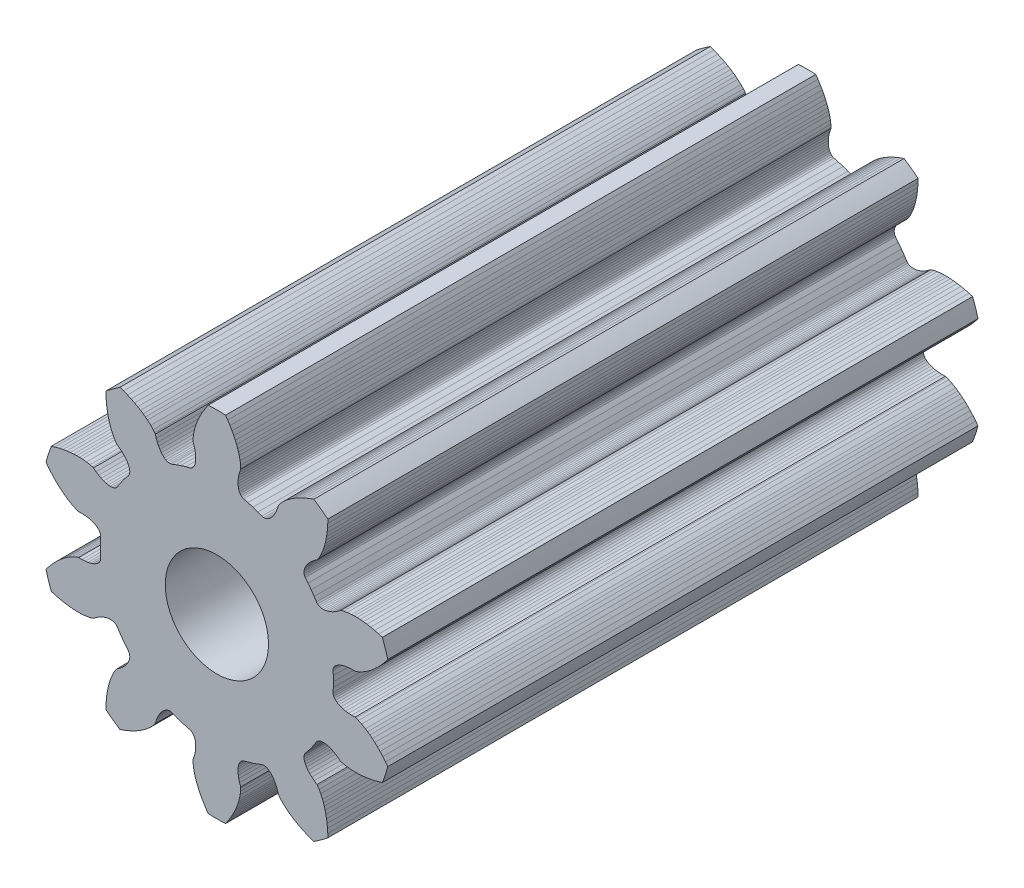
SolidWorks part; units mm, degrees
ref_plane "Front Plane" through (0, 0, 0) normal (0, 0, 1) x (1, 0, 0)
ref_plane "Top Plane" through (0, 0, 0) normal (0, 1, 0) x (1, 0, 0)
ref_plane "Right Plane" through (0, 0, 0) normal (1, 0, 0) x (0, 0, -1)
sketch "Sketch1" plane through (0, 0, 0) normal (0, 0, 1) x (1, 0, 0)
  line L0 (11.2428, -4.5485) -> (11.2517, -4.4039)
  line L1 (11.2517, -4.4039) -> (11.266, -4.2669)
  line L2 (11.266, -4.2669) -> (11.2847, -4.1393)
  line L3 (11.2847, -4.1393) -> (11.3071, -4.0209)
  line L4 (11.3071, -4.0209) -> (11.3325, -3.912)
  line L5 (11.3325, -3.912) -> (11.3608, -3.8103)
  line L6 (11.3608, -3.8103) -> (11.3897, -3.7211)
  line L7 (11.3897, -3.7211) -> (11.4208, -3.6371)
  line L8 (11.4208, -3.6371) -> (11.4807, -3.5016)
  line L9 (11.4807, -3.5016) -> (11.5377, -3.3971)
  line L10 (11.5377, -3.3971) -> (11.5845, -3.3262)
  line L11 (11.5845, -3.3262) -> (11.6076, -3.2964)
  line L12 (11.6076, -3.2964) -> (11.7007, -3.2317)
  line L13 (11.7007, -3.2317) -> (11.7827, -3.1653)
  line L14 (11.7827, -3.1653) -> (11.8533, -3.098)
  line L15 (11.8533, -3.098) -> (11.9128, -3.0308)
  line L16 (11.9128, -3.0308) -> (11.9612, -2.9643)
  line L17 (11.9612, -2.9643) -> (11.9989, -2.8995)
  line L18 (11.9989, -2.8995) -> (12.0259, -2.837)
  line L19 (12.0259, -2.837) -> (12.0426, -2.7776)
  line L20 (12.0426, -2.7776) -> (12.0493, -2.7222)
  line L21 (12.0493, -2.7222) -> (12.0463, -2.6714)
  line L22 (12.0463, -2.6714) -> (12.0342, -2.6259)
  line L23 (12.0342, -2.6259) -> (12.0067, -2.5776)
  line L24 (12.0067, -2.5776) -> (11.9109, -2.4617)
  line L25 (11.9109, -2.4617) -> (11.8044, -2.3217)
  line L26 (11.8044, -2.3217) -> (11.7041, -2.1772)
  line L27 (11.7041, -2.1772) -> (11.6236, -2.0503)
  line L28 (11.6236, -2.0503) -> (11.5861, -2.0092)
  line L29 (11.5861, -2.0092) -> (11.5466, -1.9836)
  line L30 (11.5466, -1.9836) -> (11.4992, -1.9651)
  line L31 (11.4992, -1.9651) -> (11.4444, -1.9543)
  line L32 (11.4444, -1.9543) -> (11.3828, -1.9518)
  line L33 (11.3828, -1.9518) -> (11.315, -1.9582)
  line L34 (11.315, -1.9582) -> (11.2417, -1.974)
  line L35 (11.2417, -1.974) -> (11.1635, -1.9995)
  line L36 (11.1635, -1.9995) -> (11.0812, -2.0353)
  line L37 (11.0812, -2.0353) -> (10.9954, -2.0817)
  line L38 (10.9954, -2.0817) -> (10.907, -2.1391)
  line L39 (10.907, -2.1391) -> (10.8166, -2.2077)
  line L40 (10.8166, -2.2077) -> (10.7811, -2.2204)
  line L41 (10.7811, -2.2204) -> (10.6992, -2.243)
  line L42 (10.6992, -2.243) -> (10.5823, -2.2649)
  line L43 (10.5823, -2.2649) -> (10.4348, -2.2801)
  line L44 (10.4348, -2.2801) -> (10.3453, -2.2837)
  line L45 (10.3453, -2.2837) -> (10.2516, -2.2836)
  line L46 (10.2516, -2.2836) -> (10.1461, -2.2791)
  line L47 (10.1461, -2.2791) -> (10.0348, -2.2696)
  line L48 (10.0348, -2.2696) -> (9.9151, -2.2543)
  line L49 (9.9151, -2.2543) -> (9.7881, -2.2327)
  line L50 (9.7881, -2.2327) -> (9.6533, -2.2039)
  line L51 (9.6533, -2.2039) -> (9.5131, -2.1677)
  line L52 (9.5131, -2.1677) -> (9.3912, -2.1311)
  line L53 (9.2098, -1.5726) -> (9.2868, -1.4714)
  line L54 (9.2868, -1.4714) -> (9.379, -1.3597)
  line L55 (9.379, -1.3597) -> (9.4711, -1.2572)
  line L56 (9.4711, -1.2572) -> (9.5612, -1.165)
  line L57 (9.5612, -1.165) -> (9.649, -1.0823)
  line L58 (9.649, -1.0823) -> (9.7335, -1.0092)
  line L59 (9.7335, -1.0092) -> (9.8162, -0.9435)
  line L60 (9.8162, -0.9435) -> (9.8919, -0.8883)
  line L61 (9.8919, -0.8883) -> (9.9665, -0.8387)
  line L62 (9.9665, -0.8387) -> (10.0947, -0.7642)
  line L63 (10.0947, -0.7642) -> (10.2021, -0.7133)
  line L64 (10.2021, -0.7133) -> (10.2817, -0.6834)
  line L65 (10.2817, -0.6834) -> (10.3179, -0.6728)
  line L66 (10.3179, -0.6728) -> (10.4313, -0.6752)
  line L67 (10.4313, -0.6752) -> (10.5366, -0.6696)
  line L68 (10.5366, -0.6696) -> (10.6333, -0.6568)
  line L69 (10.6333, -0.6568) -> (10.7209, -0.6373)
  line L70 (10.7209, -0.6373) -> (10.7992, -0.612)
  line L71 (10.7992, -0.612) -> (10.8678, -0.5817)
  line L72 (10.8678, -0.5817) -> (10.9263, -0.547)
  line L73 (10.9263, -0.547) -> (10.9747, -0.5088)
  line L74 (10.9747, -0.5088) -> (11.0127, -0.4679)
  line L75 (11.0127, -0.4679) -> (11.0402, -0.4251)
  line L76 (11.0402, -0.4251) -> (11.0571, -0.3811)
  line L77 (11.0571, -0.3811) -> (11.0633, -0.3259)
  line L78 (11.0633, -0.3259) -> (11.0539, -0.1759)
  line L79 (11.0539, -0.1759) -> (11.05, 0)
  line L80 (11.05, 0) -> (11.0539, 0.1759)
  line L81 (11.0539, 0.1759) -> (11.0633, 0.3259)
  line L82 (11.0633, 0.3259) -> (11.0571, 0.3812)
  line L83 (11.0571, 0.3812) -> (11.0402, 0.4251)
  line L84 (11.0402, 0.4251) -> (11.0127, 0.468)
  line L85 (11.0127, 0.468) -> (10.9747, 0.5089)
  line L86 (10.9747, 0.5089) -> (10.9263, 0.5471)
  line L87 (10.9263, 0.5471) -> (10.8678, 0.5817)
  line L88 (10.8678, 0.5817) -> (10.7992, 0.6121)
  line L89 (10.7992, 0.6121) -> (10.7209, 0.6374)
  line L90 (10.7209, 0.6374) -> (10.6333, 0.6568)
  line L91 (10.6333, 0.6568) -> (10.5366, 0.6697)
  line L92 (10.5366, 0.6697) -> (10.4313, 0.6753)
  line L93 (10.4313, 0.6753) -> (10.3179, 0.6729)
  line L94 (10.3179, 0.6729) -> (10.2817, 0.6834)
  line L95 (10.2817, 0.6834) -> (10.2021, 0.7133)
  line L96 (10.2021, 0.7133) -> (10.0947, 0.7643)
  line L97 (10.0947, 0.7643) -> (9.9665, 0.8387)
  line L98 (9.9665, 0.8387) -> (9.8919, 0.8884)
  line L99 (9.8919, 0.8884) -> (9.8162, 0.9436)
  line L100 (9.8162, 0.9436) -> (9.7335, 1.0093)
  line L101 (9.7335, 1.0093) -> (9.649, 1.0824)
  line L102 (9.649, 1.0824) -> (9.5612, 1.165)
  line L103 (9.5612, 1.165) -> (9.4711, 1.2572)
  line L104 (9.4711, 1.2572) -> (9.379, 1.3597)
  line L105 (9.379, 1.3597) -> (9.2868, 1.4714)
  line L106 (9.2868, 1.4714) -> (9.2098, 1.5727)
  line L107 (9.3912, 2.1311) -> (9.5131, 2.1677)
  line L108 (9.5131, 2.1677) -> (9.6533, 2.2039)
  line L109 (9.6533, 2.2039) -> (9.788, 2.2327)
  line L110 (9.788, 2.2327) -> (9.9151, 2.2544)
  line L111 (9.9151, 2.2544) -> (10.0347, 2.2696)
  line L112 (10.0347, 2.2696) -> (10.1461, 2.2791)
  line L113 (10.1461, 2.2791) -> (10.2516, 2.2836)
  line L114 (10.2516, 2.2836) -> (10.3453, 2.2837)
  line L115 (10.3453, 2.2837) -> (10.4348, 2.2801)
  line L116 (10.4348, 2.2801) -> (10.5823, 2.265)
  line L117 (10.5823, 2.265) -> (10.6992, 2.2431)
  line L118 (10.6992, 2.2431) -> (10.7811, 2.2205)
  line L119 (10.7811, 2.2205) -> (10.8166, 2.2078)
  line L120 (10.8166, 2.2078) -> (10.9069, 2.1391)
  line L121 (10.9069, 2.1391) -> (10.9954, 2.0818)
  line L122 (10.9954, 2.0818) -> (11.0812, 2.0353)
  line L123 (11.0812, 2.0353) -> (11.1635, 1.9995)
  line L124 (11.1635, 1.9995) -> (11.2417, 1.974)
  line L125 (11.2417, 1.974) -> (11.315, 1.9583)
  line L126 (11.315, 1.9583) -> (11.3828, 1.9519)
  line L127 (11.3828, 1.9519) -> (11.4444, 1.9543)
  line L128 (11.4444, 1.9543) -> (11.4991, 1.9651)
  line L129 (11.4991, 1.9651) -> (11.5465, 1.9836)
  line L130 (11.5465, 1.9836) -> (11.586, 2.0092)
  line L131 (11.586, 2.0092) -> (11.6235, 2.0503)
  line L132 (11.6235, 2.0503) -> (11.7041, 2.1772)
  line L133 (11.7041, 2.1772) -> (11.8043, 2.3218)
  line L134 (11.8043, 2.3218) -> (11.9109, 2.4618)
  line L135 (11.9109, 2.4618) -> (12.0067, 2.5776)
  line L136 (12.0067, 2.5776) -> (12.0341, 2.626)
  line L137 (12.0341, 2.626) -> (12.0463, 2.6715)
  line L138 (12.0463, 2.6715) -> (12.0492, 2.7223)
  line L139 (12.0492, 2.7223) -> (12.0426, 2.7777)
  line L140 (12.0426, 2.7777) -> (12.0259, 2.837)
  line L141 (12.0259, 2.837) -> (11.9988, 2.8995)
  line L142 (11.9988, 2.8995) -> (11.9612, 2.9643)
  line L143 (11.9612, 2.9643) -> (11.9128, 3.0308)
  line L144 (11.9128, 3.0308) -> (11.8533, 3.0981)
  line L145 (11.8533, 3.0981) -> (11.7826, 3.1653)
  line L146 (11.7826, 3.1653) -> (11.7007, 3.2317)
  line L147 (11.7007, 3.2317) -> (11.6075, 3.2964)
  line L148 (11.6075, 3.2964) -> (11.5845, 3.3262)
  line L149 (11.5845, 3.3262) -> (11.5377, 3.3972)
  line L150 (11.5377, 3.3972) -> (11.4807, 3.5016)
  line L151 (11.4807, 3.5016) -> (11.4208, 3.6372)
  line L152 (11.4208, 3.6372) -> (11.3896, 3.7212)
  line L153 (11.3896, 3.7212) -> (11.3608, 3.8103)
  line L154 (11.3608, 3.8103) -> (11.3325, 3.9121)
  line L155 (11.3325, 3.9121) -> (11.3071, 4.0209)
  line L156 (11.3071, 4.0209) -> (11.2846, 4.1394)
  line L157 (11.2846, 4.1394) -> (11.2659, 4.2669)
  line L158 (11.2659, 4.2669) -> (11.2517, 4.404)
  line L159 (11.2517, 4.404) -> (11.2428, 4.5485)
  line L160 (11.2428, 4.5485) -> (11.2399, 4.6757)
  line L161 (11.715, 5.0209) -> (11.8351, 4.9789)
  line L162 (11.8351, 4.9789) -> (11.9698, 4.9257)
  line L163 (11.9698, 4.9257) -> (12.0958, 4.8698)
  line L164 (12.0958, 4.8698) -> (12.2113, 4.8127)
  line L165 (12.2113, 4.8127) -> (12.3171, 4.7547)
  line L166 (12.3171, 4.7547) -> (12.4127, 4.6969)
  line L167 (12.4127, 4.6969) -> (12.5007, 4.6385)
  line L168 (12.5007, 4.6385) -> (12.5766, 4.5836)
  line L169 (12.5766, 4.5836) -> (12.6469, 4.528)
  line L170 (12.6469, 4.528) -> (12.7573, 4.4291)
  line L171 (12.7573, 4.4291) -> (12.839, 4.3427)
  line L172 (12.839, 4.3427) -> (12.892, 4.2762)
  line L173 (12.892, 4.2762) -> (12.9132, 4.2451)
  line L174 (12.9132, 4.2451) -> (12.946, 4.1364)
  line L175 (12.946, 4.1364) -> (12.9838, 4.038)
  line L176 (12.9838, 4.038) -> (13.0259, 3.9501)
  line L177 (13.0259, 3.9501) -> (13.0715, 3.8727)
  line L178 (13.0715, 3.8727) -> (13.1197, 3.8061)
  line L179 (13.1197, 3.8061) -> (13.1698, 3.7503)
  line L180 (13.1698, 3.7503) -> (13.2209, 3.7053)
  line L181 (13.2209, 3.7053) -> (13.2721, 3.671)
  line L182 (13.2721, 3.671) -> (13.3228, 3.6476)
  line L183 (13.3228, 3.6476) -> (13.372, 3.6347)
  line L184 (13.372, 3.6347) -> (13.419, 3.6322)
  line L185 (13.419, 3.6322) -> (13.4735, 3.6434)
  line L186 (13.4735, 3.6434) -> (13.6133, 3.6987)
  line L187 (13.6133, 3.6987) -> (13.7794, 3.7567)
  line L188 (13.7794, 3.7567) -> (13.9478, 3.8074)
  line L189 (13.9478, 3.8074) -> (14.0934, 3.8448)
  line L190 (14.0934, 3.8448) -> (14.1441, 3.8678)
  line L191 (14.1441, 3.8678) -> (14.1806, 3.8974)
  line L192 (14.1806, 3.8974) -> (14.2129, 3.9368)
  line L193 (14.2129, 3.9368) -> (14.2401, 3.9855)
  line L194 (14.2401, 3.9855) -> (14.2614, 4.0434)
  line L195 (14.2614, 4.0434) -> (14.2763, 4.1098)
  line L196 (14.2763, 4.1098) -> (14.284, 4.1844)
  line L197 (14.284, 4.1844) -> (14.2838, 4.2666)
  line L198 (14.2838, 4.2666) -> (14.2752, 4.356)
  line L199 (14.2752, 4.356) -> (14.2576, 4.4519)
  line L200 (14.2576, 4.4519) -> (14.2304, 4.5538)
  line L201 (14.2304, 4.5538) -> (14.193, 4.6609)
  line L202 (14.193, 4.6609) -> (14.1919, 4.6986)
  line L203 (14.1919, 4.6986) -> (14.1957, 4.7835)
  line L204 (14.1957, 4.7835) -> (14.211, 4.9014)
  line L205 (14.211, 4.9014) -> (14.2422, 5.0463)
  line L206 (14.2422, 5.0463) -> (14.2664, 5.1326)
  line L207 (14.2664, 5.1326) -> (14.2955, 5.2217)
  line L208 (14.2955, 5.2217) -> (14.3324, 5.3207)
  line L209 (14.3324, 5.3207) -> (14.3758, 5.4236)
  line L210 (14.3758, 5.4236) -> (14.4273, 5.5327)
  line L211 (14.4273, 5.5327) -> (14.4871, 5.6468)
  line L212 (14.4871, 5.6468) -> (14.5562, 5.7661)
  line L213 (14.5562, 5.7661) -> (14.6339, 5.8883)
  line L214 (14.6339, 5.8883) -> (14.7064, 5.9928)
  line L215 (15.2936, 5.9928) -> (15.3661, 5.8883)
  line L216 (15.3661, 5.8883) -> (15.4438, 5.7661)
  line L217 (15.4438, 5.7661) -> (15.5128, 5.6468)
  line L218 (15.5128, 5.6468) -> (15.5727, 5.5327)
  line L219 (15.5727, 5.5327) -> (15.6242, 5.4236)
  line L220 (15.6242, 5.4236) -> (15.6676, 5.3207)
  line L221 (15.6676, 5.3207) -> (15.7045, 5.2217)
  line L222 (15.7045, 5.2217) -> (15.7336, 5.1326)
  line L223 (15.7336, 5.1326) -> (15.7578, 5.0464)
  line L224 (15.7578, 5.0464) -> (15.7889, 4.9014)
  line L225 (15.7889, 4.9014) -> (15.8042, 4.7835)
  line L226 (15.8042, 4.7835) -> (15.8081, 4.6986)
  line L227 (15.8081, 4.6986) -> (15.8069, 4.6609)
  line L228 (15.8069, 4.6609) -> (15.7696, 4.5538)
  line L229 (15.7696, 4.5538) -> (15.7424, 4.4519)
  line L230 (15.7424, 4.4519) -> (15.7247, 4.356)
  line L231 (15.7247, 4.356) -> (15.7161, 4.2666)
  line L232 (15.7161, 4.2666) -> (15.716, 4.1844)
  line L233 (15.716, 4.1844) -> (15.7237, 4.1098)
  line L234 (15.7237, 4.1098) -> (15.7385, 4.0434)
  line L235 (15.7385, 4.0434) -> (15.7599, 3.9855)
  line L236 (15.7599, 3.9855) -> (15.7871, 3.9368)
  line L237 (15.7871, 3.9368) -> (15.8193, 3.8974)
  line L238 (15.8193, 3.8974) -> (15.8559, 3.8678)
  line L239 (15.8559, 3.8678) -> (15.9065, 3.8448)
  line L240 (15.9065, 3.8448) -> (16.0521, 3.8074)
  line L241 (16.0521, 3.8074) -> (16.2206, 3.7567)
  line L242 (16.2206, 3.7567) -> (16.3867, 3.6987)
  line L243 (16.3867, 3.6987) -> (16.5264, 3.6434)
  line L244 (16.5264, 3.6434) -> (16.5809, 3.6322)
  line L245 (16.5809, 3.6322) -> (16.6279, 3.6347)
  line L246 (16.6279, 3.6347) -> (16.6772, 3.6476)
  line L247 (16.6772, 3.6476) -> (16.7278, 3.6711)
  line L248 (16.7278, 3.6711) -> (16.7791, 3.7053)
  line L249 (16.7791, 3.7053) -> (16.8301, 3.7503)
  line L250 (16.8301, 3.7503) -> (16.8802, 3.8061)
  line L251 (16.8802, 3.8061) -> (16.9284, 3.8727)
  line L252 (16.9284, 3.8727) -> (16.974, 3.9501)
  line L253 (16.974, 3.9501) -> (17.0161, 4.038)
  line L254 (17.0161, 4.038) -> (17.054, 4.1365)
  line L255 (17.054, 4.1365) -> (17.0867, 4.2451)
  line L256 (17.0867, 4.2451) -> (17.108, 4.2762)
  line L257 (17.108, 4.2762) -> (17.161, 4.3427)
  line L258 (17.161, 4.3427) -> (17.2427, 4.4291)
  line L259 (17.2427, 4.4291) -> (17.3531, 4.528)
  line L260 (17.3531, 4.528) -> (17.4233, 4.5836)
  line L261 (17.4233, 4.5836) -> (17.4992, 4.6385)
  line L262 (17.4992, 4.6385) -> (17.5873, 4.6969)
  line L263 (17.5873, 4.6969) -> (17.6829, 4.7547)
  line L264 (17.6829, 4.7547) -> (17.7886, 4.8127)
  line L265 (17.7886, 4.8127) -> (17.9042, 4.8699)
  line L266 (17.9042, 4.8699) -> (18.0301, 4.9258)
  line L267 (18.0301, 4.9258) -> (18.1648, 4.9789)
  line L268 (18.1648, 4.9789) -> (18.2849, 5.0209)
  line L269 (18.76, 4.6758) -> (18.7572, 4.5486)
  line L270 (18.7572, 4.5486) -> (18.7483, 4.404)
  line L271 (18.7483, 4.404) -> (18.734, 4.2669)
  line L272 (18.734, 4.2669) -> (18.7153, 4.1394)
  line L273 (18.7153, 4.1394) -> (18.6928, 4.0209)
  line L274 (18.6928, 4.0209) -> (18.6675, 3.9121)
  line L275 (18.6675, 3.9121) -> (18.6392, 3.8103)
  line L276 (18.6392, 3.8103) -> (18.6103, 3.7212)
  line L277 (18.6103, 3.7212) -> (18.5792, 3.6372)
  line L278 (18.5792, 3.6372) -> (18.5192, 3.5016)
  line L279 (18.5192, 3.5016) -> (18.4623, 3.3972)
  line L280 (18.4623, 3.3972) -> (18.4155, 3.3263)
  line L281 (18.4155, 3.3263) -> (18.3924, 3.2965)
  line L282 (18.3924, 3.2965) -> (18.2992, 3.2317)
  line L283 (18.2992, 3.2317) -> (18.2173, 3.1653)
  line L284 (18.2173, 3.1653) -> (18.1467, 3.0981)
  line L285 (18.1467, 3.0981) -> (18.0872, 3.0308)
  line L286 (18.0872, 3.0308) -> (18.0387, 2.9644)
  line L287 (18.0387, 2.9644) -> (18.0011, 2.8995)
  line L288 (18.0011, 2.8995) -> (17.9741, 2.837)
  line L289 (17.9741, 2.837) -> (17.9574, 2.7777)
  line L290 (17.9574, 2.7777) -> (17.9507, 2.7223)
  line L291 (17.9507, 2.7223) -> (17.9537, 2.6715)
  line L292 (17.9537, 2.6715) -> (17.9658, 2.626)
  line L293 (17.9658, 2.626) -> (17.9933, 2.5777)
  line L294 (17.9933, 2.5777) -> (18.0891, 2.4618)
  line L295 (18.0891, 2.4618) -> (18.1956, 2.3218)
  line L296 (18.1956, 2.3218) -> (18.2959, 2.1772)
  line L297 (18.2959, 2.1772) -> (18.3764, 2.0503)
  line L298 (18.3764, 2.0503) -> (18.4139, 2.0093)
  line L299 (18.4139, 2.0093) -> (18.4534, 1.9836)
  line L300 (18.4534, 1.9836) -> (18.5008, 1.9651)
  line L301 (18.5008, 1.9651) -> (18.5556, 1.9544)
  line L302 (18.5556, 1.9544) -> (18.6172, 1.9519)
  line L303 (18.6172, 1.9519) -> (18.6849, 1.9583)
  line L304 (18.6849, 1.9583) -> (18.7583, 1.974)
  line L305 (18.7583, 1.974) -> (18.8364, 1.9996)
  line L306 (18.8364, 1.9996) -> (18.9188, 2.0354)
  line L307 (18.9188, 2.0354) -> (19.0046, 2.0818)
  line L308 (19.0046, 2.0818) -> (19.093, 2.1392)
  line L309 (19.093, 2.1392) -> (19.1834, 2.2078)
  line L310 (19.1834, 2.2078) -> (19.2188, 2.2205)
  line L311 (19.2188, 2.2205) -> (19.3008, 2.2431)
  line L312 (19.3008, 2.2431) -> (19.4177, 2.265)
  line L313 (19.4177, 2.265) -> (19.5651, 2.2801)
  line L314 (19.5651, 2.2801) -> (19.6547, 2.2838)
  line L315 (19.6547, 2.2838) -> (19.7484, 2.2837)
  line L316 (19.7484, 2.2837) -> (19.8539, 2.2791)
  line L317 (19.8539, 2.2791) -> (19.9652, 2.2696)
  line L318 (19.9652, 2.2696) -> (20.0848, 2.2544)
  line L319 (20.0848, 2.2544) -> (20.2119, 2.2328)
  line L320 (20.2119, 2.2328) -> (20.3467, 2.204)
  line L321 (20.3467, 2.204) -> (20.4869, 2.1678)
  line L322 (20.4869, 2.1678) -> (20.6088, 2.1312)
  line L323 (20.7902, 1.5727) -> (20.7132, 1.4714)
  line L324 (20.7132, 1.4714) -> (20.621, 1.3598)
  line L325 (20.621, 1.3598) -> (20.5289, 1.2572)
  line L326 (20.5289, 1.2572) -> (20.4388, 1.165)
  line L327 (20.4388, 1.165) -> (20.351, 1.0824)
  line L328 (20.351, 1.0824) -> (20.2665, 1.0093)
  line L329 (20.2665, 1.0093) -> (20.1838, 0.9436)
  line L330 (20.1838, 0.9436) -> (20.108, 0.8884)
  line L331 (20.108, 0.8884) -> (20.0335, 0.8388)
  line L332 (20.0335, 0.8388) -> (19.9053, 0.7643)
  line L333 (19.9053, 0.7643) -> (19.7979, 0.7133)
  line L334 (19.7979, 0.7133) -> (19.7183, 0.6834)
  line L335 (19.7183, 0.6834) -> (19.6821, 0.6729)
  line L336 (19.6821, 0.6729) -> (19.5687, 0.6753)
  line L337 (19.5687, 0.6753) -> (19.4634, 0.6697)
  line L338 (19.4634, 0.6697) -> (19.3667, 0.6568)
  line L339 (19.3667, 0.6568) -> (19.279, 0.6374)
  line L340 (19.279, 0.6374) -> (19.2008, 0.6121)
  line L341 (19.2008, 0.6121) -> (19.1322, 0.5818)
  line L342 (19.1322, 0.5818) -> (19.0736, 0.5471)
  line L343 (19.0736, 0.5471) -> (19.0253, 0.5089)
  line L344 (19.0253, 0.5089) -> (18.9873, 0.468)
  line L345 (18.9873, 0.468) -> (18.9598, 0.4252)
  line L346 (18.9598, 0.4252) -> (18.9429, 0.3812)
  line L347 (18.9429, 0.3812) -> (18.9367, 0.3259)
  line L348 (18.9367, 0.3259) -> (18.9461, 0.1759)
  line L349 (18.9461, 0.1759) -> (18.95, 0)
  line L350 (18.95, 0) -> (18.9461, -0.1758)
  line L351 (18.9461, -0.1758) -> (18.9367, -0.3259)
  line L352 (18.9367, -0.3259) -> (18.9429, -0.3811)
  line L353 (18.9429, -0.3811) -> (18.9598, -0.4251)
  line L354 (18.9598, -0.4251) -> (18.9873, -0.4679)
  line L355 (18.9873, -0.4679) -> (19.0253, -0.5088)
  line L356 (19.0253, -0.5088) -> (19.0736, -0.547)
  line L357 (19.0736, -0.547) -> (19.1322, -0.5817)
  line L358 (19.1322, -0.5817) -> (19.2008, -0.612)
  line L359 (19.2008, -0.612) -> (19.279, -0.6373)
  line L360 (19.279, -0.6373) -> (19.3667, -0.6567)
  line L361 (19.3667, -0.6567) -> (19.4634, -0.6696)
  line L362 (19.4634, -0.6696) -> (19.5687, -0.6752)
  line L363 (19.5687, -0.6752) -> (19.6821, -0.6728)
  line L364 (19.6821, -0.6728) -> (19.7183, -0.6834)
  line L365 (19.7183, -0.6834) -> (19.7979, -0.7132)
  line L366 (19.7979, -0.7132) -> (19.9053, -0.7642)
  line L367 (19.9053, -0.7642) -> (20.0335, -0.8387)
  line L368 (20.0335, -0.8387) -> (20.108, -0.8883)
  line L369 (20.108, -0.8883) -> (20.1838, -0.9435)
  line L370 (20.1838, -0.9435) -> (20.2665, -1.0092)
  line L371 (20.2665, -1.0092) -> (20.351, -1.0823)
  line L372 (20.351, -1.0823) -> (20.4388, -1.1649)
  line L373 (20.4388, -1.1649) -> (20.5289, -1.2571)
  line L374 (20.5289, -1.2571) -> (20.621, -1.3597)
  line L375 (20.621, -1.3597) -> (20.7132, -1.4714)
  line L376 (20.7132, -1.4714) -> (20.7902, -1.5726)
  line L377 (20.6088, -2.131) -> (20.4869, -2.1677)
  line L378 (20.4869, -2.1677) -> (20.3467, -2.2039)
  line L379 (20.3467, -2.2039) -> (20.2119, -2.2327)
  line L380 (20.2119, -2.2327) -> (20.0849, -2.2543)
  line L381 (20.0849, -2.2543) -> (19.9652, -2.2695)
  line L382 (19.9652, -2.2695) -> (19.8539, -2.279)
  line L383 (19.8539, -2.279) -> (19.7484, -2.2836)
  line L384 (19.7484, -2.2836) -> (19.6547, -2.2837)
  line L385 (19.6547, -2.2837) -> (19.5652, -2.28)
  line L386 (19.5652, -2.28) -> (19.4177, -2.2649)
  line L387 (19.4177, -2.2649) -> (19.3008, -2.243)
  line L388 (19.3008, -2.243) -> (19.2189, -2.2204)
  line L389 (19.2189, -2.2204) -> (19.1834, -2.2077)
  line L390 (19.1834, -2.2077) -> (19.093, -2.1391)
  line L391 (19.093, -2.1391) -> (19.0046, -2.0817)
  line L392 (19.0046, -2.0817) -> (18.9188, -2.0353)
  line L393 (18.9188, -2.0353) -> (18.8365, -1.9995)
  line L394 (18.8365, -1.9995) -> (18.7583, -1.9739)
  line L395 (18.7583, -1.9739) -> (18.685, -1.9582)
  line L396 (18.685, -1.9582) -> (18.6172, -1.9518)
  line L397 (18.6172, -1.9518) -> (18.5556, -1.9543)
  line L398 (18.5556, -1.9543) -> (18.5008, -1.965)
  line L399 (18.5008, -1.965) -> (18.4534, -1.9835)
  line L400 (18.4534, -1.9835) -> (18.4139, -2.0092)
  line L401 (18.4139, -2.0092) -> (18.3764, -2.0502)
  line L402 (18.3764, -2.0502) -> (18.2959, -2.1771)
  line L403 (18.2959, -2.1771) -> (18.1956, -2.3217)
  line L404 (18.1956, -2.3217) -> (18.0891, -2.4617)
  line L405 (18.0891, -2.4617) -> (17.9933, -2.5776)
  line L406 (17.9933, -2.5776) -> (17.9658, -2.6259)
  line L407 (17.9658, -2.6259) -> (17.9537, -2.6714)
  line L408 (17.9537, -2.6714) -> (17.9507, -2.7222)
  line L409 (17.9507, -2.7222) -> (17.9574, -2.7776)
  line L410 (17.9574, -2.7776) -> (17.9741, -2.8369)
  line L411 (17.9741, -2.8369) -> (18.0011, -2.8994)
  line L412 (18.0011, -2.8994) -> (18.0387, -2.9643)
  line L413 (18.0387, -2.9643) -> (18.0872, -3.0307)
  line L414 (18.0872, -3.0307) -> (18.1467, -3.098)
  line L415 (18.1467, -3.098) -> (18.2173, -3.1652)
  line L416 (18.2173, -3.1652) -> (18.2992, -3.2316)
  line L417 (18.2992, -3.2316) -> (18.3924, -3.2964)
  line L418 (18.3924, -3.2964) -> (18.4155, -3.3262)
  line L419 (18.4155, -3.3262) -> (18.4623, -3.3971)
  line L420 (18.4623, -3.3971) -> (18.5193, -3.5015)
  line L421 (18.5193, -3.5015) -> (18.5792, -3.6371)
  line L422 (18.5792, -3.6371) -> (18.6103, -3.7211)
  line L423 (18.6103, -3.7211) -> (18.6392, -3.8102)
  line L424 (18.6392, -3.8102) -> (18.6675, -3.912)
  line L425 (18.6675, -3.912) -> (18.6929, -4.0208)
  line L426 (18.6929, -4.0208) -> (18.7153, -4.1393)
  line L427 (18.7153, -4.1393) -> (18.734, -4.2668)
  line L428 (18.734, -4.2668) -> (18.7483, -4.4039)
  line L429 (18.7483, -4.4039) -> (18.7572, -4.5484)
  line L430 (18.7572, -4.5484) -> (18.76, -4.6757)
  line L431 (18.285, -5.0208) -> (18.1648, -4.9788)
  line L432 (18.1648, -4.9788) -> (18.0301, -4.9257)
  line L433 (18.0301, -4.9257) -> (17.9042, -4.8698)
  line L434 (17.9042, -4.8698) -> (17.7886, -4.8126)
  line L435 (17.7886, -4.8126) -> (17.6829, -4.7546)
  line L436 (17.6829, -4.7546) -> (17.5873, -4.6968)
  line L437 (17.5873, -4.6968) -> (17.4992, -4.6385)
  line L438 (17.4992, -4.6385) -> (17.4234, -4.5835)
  line L439 (17.4234, -4.5835) -> (17.3531, -4.5279)
  line L440 (17.3531, -4.5279) -> (17.2427, -4.429)
  line L441 (17.2427, -4.429) -> (17.161, -4.3426)
  line L442 (17.161, -4.3426) -> (17.108, -4.2761)
  line L443 (17.108, -4.2761) -> (17.0868, -4.245)
  line L444 (17.0868, -4.245) -> (17.054, -4.1364)
  line L445 (17.054, -4.1364) -> (17.0161, -4.038)
  line L446 (17.0161, -4.038) -> (16.974, -3.95)
  line L447 (16.974, -3.95) -> (16.9284, -3.8726)
  line L448 (16.9284, -3.8726) -> (16.8802, -3.806)
  line L449 (16.8802, -3.806) -> (16.8302, -3.7502)
  line L450 (16.8302, -3.7502) -> (16.7791, -3.7052)
  line L451 (16.7791, -3.7052) -> (16.7278, -3.671)
  line L452 (16.7278, -3.671) -> (16.6772, -3.6475)
  line L453 (16.6772, -3.6475) -> (16.6279, -3.6346)
  line L454 (16.6279, -3.6346) -> (16.5809, -3.6321)
  line L455 (16.5809, -3.6321) -> (16.5265, -3.6433)
  line L456 (16.5265, -3.6433) -> (16.3867, -3.6986)
  line L457 (16.3867, -3.6986) -> (16.2206, -3.7567)
  line L458 (16.2206, -3.7567) -> (16.0521, -3.8073)
  line L459 (16.0521, -3.8073) -> (15.9066, -3.8447)
  line L460 (15.9066, -3.8447) -> (15.8559, -3.8677)
  line L461 (15.8559, -3.8677) -> (15.8193, -3.8973)
  line L462 (15.8193, -3.8973) -> (15.7871, -3.9367)
  line L463 (15.7871, -3.9367) -> (15.7599, -3.9855)
  line L464 (15.7599, -3.9855) -> (15.7385, -4.0433)
  line L465 (15.7385, -4.0433) -> (15.7237, -4.1097)
  line L466 (15.7237, -4.1097) -> (15.716, -4.1843)
  line L467 (15.716, -4.1843) -> (15.7161, -4.2665)
  line L468 (15.7161, -4.2665) -> (15.7247, -4.3559)
  line L469 (15.7247, -4.3559) -> (15.7424, -4.4518)
  line L470 (15.7424, -4.4518) -> (15.7696, -4.5537)
  line L471 (15.7696, -4.5537) -> (15.8069, -4.6609)
  line L472 (15.8069, -4.6609) -> (15.8081, -4.6985)
  line L473 (15.8081, -4.6985) -> (15.8042, -4.7834)
  line L474 (15.8042, -4.7834) -> (15.789, -4.9014)
  line L475 (15.789, -4.9014) -> (15.7578, -5.0463)
  line L476 (15.7578, -5.0463) -> (15.7336, -5.1325)
  line L477 (15.7336, -5.1325) -> (15.7045, -5.2216)
  line L478 (15.7045, -5.2216) -> (15.6676, -5.3206)
  line L479 (15.6676, -5.3206) -> (15.6242, -5.4235)
  line L480 (15.6242, -5.4235) -> (15.5727, -5.5326)
  line L481 (15.5727, -5.5326) -> (15.5129, -5.6468)
  line L482 (15.5129, -5.6468) -> (15.4438, -5.766)
  line L483 (15.4438, -5.766) -> (15.3661, -5.8882)
  line L484 (15.3661, -5.8882) -> (15.2936, -5.9928)
  line L485 (14.7064, -5.9928) -> (14.6339, -5.8882)
  line L486 (14.6339, -5.8882) -> (14.5561, -5.766)
  line L487 (14.5561, -5.766) -> (14.4871, -5.6468)
  line L488 (14.4871, -5.6468) -> (14.4272, -5.5326)
  line L489 (14.4272, -5.5326) -> (14.3758, -5.4235)
  line L490 (14.3758, -5.4235) -> (14.3324, -5.3206)
  line L491 (14.3324, -5.3206) -> (14.2954, -5.2216)
  line L492 (14.2954, -5.2216) -> (14.2664, -5.1325)
  line L493 (14.2664, -5.1325) -> (14.2422, -5.0463)
  line L494 (14.2422, -5.0463) -> (14.211, -4.9014)
  line L495 (14.211, -4.9014) -> (14.1957, -4.7834)
  line L496 (14.1957, -4.7834) -> (14.1919, -4.6985)
  line L497 (14.1919, -4.6985) -> (14.193, -4.6608)
  line L498 (14.193, -4.6608) -> (14.2304, -4.5537)
  line L499 (14.2304, -4.5537) -> (14.2576, -4.4518)
  line L500 (14.2576, -4.4518) -> (14.2752, -4.3559)
  line L501 (14.2752, -4.3559) -> (14.2838, -4.2665)
  line L502 (14.2838, -4.2665) -> (14.284, -4.1843)
  line L503 (14.284, -4.1843) -> (14.2763, -4.1097)
  line L504 (14.2763, -4.1097) -> (14.2614, -4.0433)
  line L505 (14.2614, -4.0433) -> (14.24, -3.9855)
  line L506 (14.24, -3.9855) -> (14.2129, -3.9367)
  line L507 (14.2129, -3.9367) -> (14.1806, -3.8973)
  line L508 (14.1806, -3.8973) -> (14.144, -3.8677)
  line L509 (14.144, -3.8677) -> (14.0934, -3.8447)
  line L510 (14.0934, -3.8447) -> (13.9478, -3.8073)
  line L511 (13.9478, -3.8073) -> (13.7793, -3.7567)
  line L512 (13.7793, -3.7567) -> (13.6133, -3.6986)
  line L513 (13.6133, -3.6986) -> (13.4735, -3.6433)
  line L514 (13.4735, -3.6433) -> (13.419, -3.6321)
  line L515 (13.419, -3.6321) -> (13.372, -3.6346)
  line L516 (13.372, -3.6346) -> (13.3228, -3.6475)
  line L517 (13.3228, -3.6475) -> (13.2721, -3.671)
  line L518 (13.2721, -3.671) -> (13.2209, -3.7052)
  line L519 (13.2209, -3.7052) -> (13.1698, -3.7502)
  line L520 (13.1698, -3.7502) -> (13.1197, -3.806)
  line L521 (13.1197, -3.806) -> (13.0715, -3.8726)
  line L522 (13.0715, -3.8726) -> (13.0259, -3.95)
  line L523 (13.0259, -3.95) -> (12.9838, -4.038)
  line L524 (12.9838, -4.038) -> (12.946, -4.1364)
  line L525 (12.946, -4.1364) -> (12.9132, -4.245)
  line L526 (12.9132, -4.245) -> (12.892, -4.2761)
  line L527 (12.892, -4.2761) -> (12.839, -4.3426)
  line L528 (12.839, -4.3426) -> (12.7573, -4.429)
  line L529 (12.7573, -4.429) -> (12.6469, -4.5279)
  line L530 (12.6469, -4.5279) -> (12.5766, -4.5835)
  line L531 (12.5766, -4.5835) -> (12.5007, -4.6385)
  line L532 (12.5007, -4.6385) -> (12.4127, -4.6968)
  line L533 (12.4127, -4.6968) -> (12.317, -4.7546)
  line L534 (12.317, -4.7546) -> (12.2113, -4.8126)
  line L535 (12.2113, -4.8126) -> (12.0958, -4.8698)
  line L536 (12.0958, -4.8698) -> (11.9698, -4.9257)
  line L537 (11.9698, -4.9257) -> (11.8351, -4.9788)
  line L538 (11.8351, -4.9788) -> (11.715, -5.0208)
  line L539 (11.24, -4.6757) -> (11.2428, -4.5485)
  line L540 (11.2428, -4.5485) -> (11.2517, -4.4039)
  line L541 (11.2517, -4.4039) -> (11.266, -4.2669)
  line L542 (11.266, -4.2669) -> (11.2847, -4.1393)
  line L543 (11.2847, -4.1393) -> (11.3071, -4.0209)
  line L544 (11.3071, -4.0209) -> (11.3325, -3.912)
  line L545 (11.3325, -3.912) -> (11.3608, -3.8103)
  line L546 (11.3608, -3.8103) -> (11.3897, -3.7211)
  line L547 (11.3897, -3.7211) -> (11.4208, -3.6371)
  line L548 (11.4208, -3.6371) -> (11.4807, -3.5016)
  line L549 (11.4807, -3.5016) -> (11.5377, -3.3971)
  line L550 (11.5377, -3.3971) -> (11.5845, -3.3262)
  line L551 (11.5845, -3.3262) -> (11.6076, -3.2964)
  line L552 (11.6076, -3.2964) -> (11.7007, -3.2317)
  line L553 (11.7007, -3.2317) -> (11.7827, -3.1653)
  line L554 (11.7827, -3.1653) -> (11.8533, -3.098)
  line L555 (11.8533, -3.098) -> (11.9128, -3.0308)
  line L556 (11.9128, -3.0308) -> (11.9612, -2.9643)
  line L557 (11.9612, -2.9643) -> (11.9989, -2.8995)
  line L558 (11.9989, -2.8995) -> (12.0259, -2.837)
  line L559 (12.0259, -2.837) -> (12.0426, -2.7776)
  line L560 (12.0426, -2.7776) -> (12.0493, -2.7222)
  line L561 (12.0493, -2.7222) -> (12.0463, -2.6714)
  line L562 (12.0463, -2.6714) -> (12.0342, -2.6259)
  line L563 (12.0342, -2.6259) -> (12.0067, -2.5776)
  line L564 (12.0067, -2.5776) -> (11.9109, -2.4617)
  line L565 (11.9109, -2.4617) -> (11.8044, -2.3217)
  line L566 (11.8044, -2.3217) -> (11.7041, -2.1772)
  line L567 (11.7041, -2.1772) -> (11.6236, -2.0503)
  line L568 (11.6236, -2.0503) -> (11.5861, -2.0092)
  line L569 (11.5861, -2.0092) -> (11.5466, -1.9836)
  line L570 (11.5466, -1.9836) -> (11.4992, -1.9651)
  line L571 (11.4992, -1.9651) -> (11.4444, -1.9543)
  line L572 (11.4444, -1.9543) -> (11.3828, -1.9518)
  line L573 (11.3828, -1.9518) -> (11.315, -1.9582)
  line L574 (11.315, -1.9582) -> (11.2417, -1.974)
  line L575 (11.2417, -1.974) -> (11.1635, -1.9995)
  line L576 (11.1635, -1.9995) -> (11.0812, -2.0353)
  line L577 (11.0812, -2.0353) -> (10.9954, -2.0817)
  line L578 (10.9954, -2.0817) -> (10.907, -2.1391)
  line L579 (10.907, -2.1391) -> (10.8166, -2.2077)
  line L580 (10.8166, -2.2077) -> (10.7811, -2.2204)
  line L581 (10.7811, -2.2204) -> (10.6992, -2.243)
  line L582 (10.6992, -2.243) -> (10.5823, -2.2649)
  line L583 (10.5823, -2.2649) -> (10.4348, -2.2801)
  line L584 (10.4348, -2.2801) -> (10.3453, -2.2837)
  line L585 (10.3453, -2.2837) -> (10.2516, -2.2836)
  line L586 (10.2516, -2.2836) -> (10.1461, -2.2791)
  line L587 (10.1461, -2.2791) -> (10.0348, -2.2696)
  line L588 (10.0348, -2.2696) -> (9.9151, -2.2543)
  line L589 (9.9151, -2.2543) -> (9.7881, -2.2327)
  line L590 (9.7881, -2.2327) -> (9.6533, -2.2039)
  line L591 (9.6533, -2.2039) -> (9.5131, -2.1677)
  line L592 (9.5131, -2.1677) -> (9.3912, -2.1311)
  line L593 (9.2098, -1.5726) -> (9.2868, -1.4714)
  line L594 (9.2868, -1.4714) -> (9.379, -1.3597)
  line L595 (9.379, -1.3597) -> (9.4711, -1.2572)
  line L596 (9.4711, -1.2572) -> (9.5612, -1.165)
  line L597 (9.5612, -1.165) -> (9.649, -1.0823)
  line L598 (9.649, -1.0823) -> (9.7335, -1.0092)
  line L599 (9.7335, -1.0092) -> (9.8162, -0.9435)
  line L600 (9.8162, -0.9435) -> (9.8919, -0.8883)
  line L601 (9.8919, -0.8883) -> (9.9665, -0.8387)
  line L602 (9.9665, -0.8387) -> (10.0947, -0.7642)
  line L603 (10.0947, -0.7642) -> (10.2021, -0.7133)
  line L604 (10.2021, -0.7133) -> (10.2817, -0.6834)
  line L605 (10.2817, -0.6834) -> (10.3179, -0.6728)
  line L606 (10.3179, -0.6728) -> (10.4313, -0.6752)
  line L607 (10.4313, -0.6752) -> (10.5366, -0.6696)
  line L608 (10.5366, -0.6696) -> (10.6333, -0.6568)
  line L609 (10.6333, -0.6568) -> (10.7209, -0.6373)
  line L610 (10.7209, -0.6373) -> (10.7992, -0.612)
  line L611 (10.7992, -0.612) -> (10.8678, -0.5817)
  line L612 (10.8678, -0.5817) -> (10.9263, -0.547)
  line L613 (10.9263, -0.547) -> (10.9747, -0.5088)
  line L614 (10.9747, -0.5088) -> (11.0127, -0.4679)
  line L615 (11.0127, -0.4679) -> (11.0402, -0.4251)
  line L616 (11.0402, -0.4251) -> (11.0571, -0.3811)
  line L617 (11.0571, -0.3811) -> (11.0633, -0.3259)
  line L618 (11.0633, -0.3259) -> (11.0539, -0.1759)
  line L619 (11.0539, -0.1759) -> (11.05, 0)
  line L620 (11.05, 0) -> (11.0539, 0.1759)
  line L621 (11.0539, 0.1759) -> (11.0633, 0.3259)
  line L622 (11.0633, 0.3259) -> (11.0571, 0.3812)
  line L623 (11.0571, 0.3812) -> (11.0402, 0.4251)
  line L624 (11.0402, 0.4251) -> (11.0127, 0.468)
  line L625 (11.0127, 0.468) -> (10.9747, 0.5089)
  line L626 (10.9747, 0.5089) -> (10.9263, 0.5471)
  line L627 (10.9263, 0.5471) -> (10.8678, 0.5817)
  line L628 (10.8678, 0.5817) -> (10.7992, 0.6121)
  line L629 (10.7992, 0.6121) -> (10.7209, 0.6374)
  line L630 (10.7209, 0.6374) -> (10.6333, 0.6568)
  line L631 (10.6333, 0.6568) -> (10.5366, 0.6697)
  line L632 (10.5366, 0.6697) -> (10.4313, 0.6753)
  line L633 (10.4313, 0.6753) -> (10.3179, 0.6729)
  line L634 (10.3179, 0.6729) -> (10.2817, 0.6834)
  line L635 (10.2817, 0.6834) -> (10.2021, 0.7133)
  line L636 (10.2021, 0.7133) -> (10.0947, 0.7643)
  line L637 (10.0947, 0.7643) -> (9.9665, 0.8387)
  line L638 (9.9665, 0.8387) -> (9.8919, 0.8884)
  line L639 (9.8919, 0.8884) -> (9.8162, 0.9436)
  line L640 (9.8162, 0.9436) -> (9.7335, 1.0093)
  line L641 (9.7335, 1.0093) -> (9.649, 1.0824)
  line L642 (9.649, 1.0824) -> (9.5612, 1.165)
  line L643 (9.5612, 1.165) -> (9.4711, 1.2572)
  line L644 (9.4711, 1.2572) -> (9.379, 1.3597)
  line L645 (9.379, 1.3597) -> (9.2868, 1.4714)
  line L646 (9.2868, 1.4714) -> (9.2098, 1.5727)
  line L647 (9.3912, 2.1311) -> (9.5131, 2.1677)
  line L648 (9.5131, 2.1677) -> (9.6533, 2.2039)
  line L649 (9.6533, 2.2039) -> (9.788, 2.2327)
  line L650 (9.788, 2.2327) -> (9.9151, 2.2544)
  line L651 (9.9151, 2.2544) -> (10.0347, 2.2696)
  line L652 (10.0347, 2.2696) -> (10.1461, 2.2791)
  line L653 (10.1461, 2.2791) -> (10.2516, 2.2836)
  line L654 (10.2516, 2.2836) -> (10.3453, 2.2837)
  line L655 (10.3453, 2.2837) -> (10.4348, 2.2801)
  line L656 (10.4348, 2.2801) -> (10.5823, 2.265)
  line L657 (10.5823, 2.265) -> (10.6992, 2.2431)
  line L658 (10.6992, 2.2431) -> (10.7811, 2.2205)
  line L659 (10.7811, 2.2205) -> (10.8166, 2.2078)
  line L660 (10.8166, 2.2078) -> (10.9069, 2.1391)
  line L661 (10.9069, 2.1391) -> (10.9954, 2.0818)
  line L662 (10.9954, 2.0818) -> (11.0812, 2.0353)
  line L663 (11.0812, 2.0353) -> (11.1635, 1.9995)
  line L664 (11.1635, 1.9995) -> (11.2417, 1.974)
  line L665 (11.2417, 1.974) -> (11.315, 1.9583)
  line L666 (11.315, 1.9583) -> (11.3828, 1.9519)
  line L667 (11.3828, 1.9519) -> (11.4444, 1.9543)
  line L668 (11.4444, 1.9543) -> (11.4991, 1.9651)
  line L669 (11.4991, 1.9651) -> (11.5465, 1.9836)
  line L670 (11.5465, 1.9836) -> (11.586, 2.0092)
  line L671 (11.586, 2.0092) -> (11.6235, 2.0503)
  line L672 (11.6235, 2.0503) -> (11.7041, 2.1772)
  line L673 (11.7041, 2.1772) -> (11.8043, 2.3218)
  line L674 (11.8043, 2.3218) -> (11.9109, 2.4618)
  line L675 (11.9109, 2.4618) -> (12.0067, 2.5776)
  line L676 (12.0067, 2.5776) -> (12.0341, 2.626)
  line L677 (12.0341, 2.626) -> (12.0463, 2.6715)
  line L678 (12.0463, 2.6715) -> (12.0492, 2.7223)
  line L679 (12.0492, 2.7223) -> (12.0426, 2.7777)
  line L680 (12.0426, 2.7777) -> (12.0259, 2.837)
  line L681 (12.0259, 2.837) -> (11.9988, 2.8995)
  line L682 (11.9988, 2.8995) -> (11.9612, 2.9643)
  line L683 (11.9612, 2.9643) -> (11.9128, 3.0308)
  line L684 (11.9128, 3.0308) -> (11.8533, 3.0981)
  line L685 (11.8533, 3.0981) -> (11.7826, 3.1653)
  line L686 (11.7826, 3.1653) -> (11.7007, 3.2317)
  line L687 (11.7007, 3.2317) -> (11.6075, 3.2964)
  line L688 (11.6075, 3.2964) -> (11.5845, 3.3262)
  line L689 (11.5845, 3.3262) -> (11.5377, 3.3972)
  line L690 (11.5377, 3.3972) -> (11.4807, 3.5016)
  line L691 (11.4807, 3.5016) -> (11.4208, 3.6372)
  line L692 (11.4208, 3.6372) -> (11.3896, 3.7212)
  line L693 (11.3896, 3.7212) -> (11.3608, 3.8103)
  line L694 (11.3608, 3.8103) -> (11.3325, 3.9121)
  line L695 (11.3325, 3.9121) -> (11.3071, 4.0209)
  line L696 (11.3071, 4.0209) -> (11.2846, 4.1394)
  line L697 (11.2846, 4.1394) -> (11.2659, 4.2669)
  line L698 (11.2659, 4.2669) -> (11.2517, 4.404)
  line L699 (11.2517, 4.404) -> (11.2428, 4.5485)
  line L700 (11.2428, 4.5485) -> (11.2399, 4.6757)
  line L701 (11.715, 5.0209) -> (11.8351, 4.9789)
  line L702 (11.8351, 4.9789) -> (11.9698, 4.9257)
  line L703 (11.9698, 4.9257) -> (12.0958, 4.8698)
  line L704 (12.0958, 4.8698) -> (12.2113, 4.8127)
  line L705 (12.2113, 4.8127) -> (12.3171, 4.7547)
  line L706 (12.3171, 4.7547) -> (12.4127, 4.6969)
  line L707 (12.4127, 4.6969) -> (12.5007, 4.6385)
  line L708 (12.5007, 4.6385) -> (12.5766, 4.5836)
  line L709 (12.5766, 4.5836) -> (12.6469, 4.528)
  line L710 (12.6469, 4.528) -> (12.7573, 4.4291)
  line L711 (12.7573, 4.4291) -> (12.839, 4.3427)
  line L712 (12.839, 4.3427) -> (12.892, 4.2762)
  line L713 (12.892, 4.2762) -> (12.9132, 4.2451)
  line L714 (12.9132, 4.2451) -> (12.946, 4.1364)
  line L715 (12.946, 4.1364) -> (12.9838, 4.038)
  line L716 (12.9838, 4.038) -> (13.0259, 3.9501)
  line L717 (13.0259, 3.9501) -> (13.0715, 3.8727)
  line L718 (13.0715, 3.8727) -> (13.1197, 3.8061)
  line L719 (13.1197, 3.8061) -> (13.1698, 3.7503)
  line L720 (13.1698, 3.7503) -> (13.2209, 3.7053)
  line L721 (13.2209, 3.7053) -> (13.2721, 3.671)
  line L722 (13.2721, 3.671) -> (13.3228, 3.6476)
  line L723 (13.3228, 3.6476) -> (13.372, 3.6347)
  line L724 (13.372, 3.6347) -> (13.419, 3.6322)
  line L725 (13.419, 3.6322) -> (13.4735, 3.6434)
  line L726 (13.4735, 3.6434) -> (13.6133, 3.6987)
  line L727 (13.6133, 3.6987) -> (13.7794, 3.7567)
  line L728 (13.7794, 3.7567) -> (13.9478, 3.8074)
  line L729 (13.9478, 3.8074) -> (14.0934, 3.8448)
  line L730 (14.0934, 3.8448) -> (14.1441, 3.8678)
  line L731 (14.1441, 3.8678) -> (14.1806, 3.8974)
  line L732 (14.1806, 3.8974) -> (14.2129, 3.9368)
  line L733 (14.2129, 3.9368) -> (14.2401, 3.9855)
  line L734 (14.2401, 3.9855) -> (14.2614, 4.0434)
  line L735 (14.2614, 4.0434) -> (14.2763, 4.1098)
  line L736 (14.2763, 4.1098) -> (14.284, 4.1844)
  line L737 (14.284, 4.1844) -> (14.2838, 4.2666)
  line L738 (14.2838, 4.2666) -> (14.2752, 4.356)
  line L739 (14.2752, 4.356) -> (14.2576, 4.4519)
  line L740 (14.2576, 4.4519) -> (14.2304, 4.5538)
  line L741 (14.2304, 4.5538) -> (14.193, 4.6609)
  line L742 (14.193, 4.6609) -> (14.1919, 4.6986)
  line L743 (14.1919, 4.6986) -> (14.1957, 4.7835)
  line L744 (14.1957, 4.7835) -> (14.211, 4.9014)
  line L745 (14.211, 4.9014) -> (14.2422, 5.0463)
  line L746 (14.2422, 5.0463) -> (14.2664, 5.1326)
  line L747 (14.2664, 5.1326) -> (14.2955, 5.2217)
  line L748 (14.2955, 5.2217) -> (14.3324, 5.3207)
  line L749 (14.3324, 5.3207) -> (14.3758, 5.4236)
  line L750 (14.3758, 5.4236) -> (14.4273, 5.5327)
  line L751 (14.4273, 5.5327) -> (14.4871, 5.6468)
  line L752 (14.4871, 5.6468) -> (14.5562, 5.7661)
  line L753 (14.5562, 5.7661) -> (14.6339, 5.8883)
  line L754 (14.6339, 5.8883) -> (14.7064, 5.9928)
  line L755 (15.2936, 5.9928) -> (15.3661, 5.8883)
  line L756 (15.3661, 5.8883) -> (15.4438, 5.7661)
  line L757 (15.4438, 5.7661) -> (15.5128, 5.6468)
  line L758 (15.5128, 5.6468) -> (15.5727, 5.5327)
  line L759 (15.5727, 5.5327) -> (15.6242, 5.4236)
  line L760 (15.6242, 5.4236) -> (15.6676, 5.3207)
  line L761 (15.6676, 5.3207) -> (15.7045, 5.2217)
  line L762 (15.7045, 5.2217) -> (15.7336, 5.1326)
  line L763 (15.7336, 5.1326) -> (15.7578, 5.0464)
  line L764 (15.7578, 5.0464) -> (15.7889, 4.9014)
  line L765 (15.7889, 4.9014) -> (15.8042, 4.7835)
  line L766 (15.8042, 4.7835) -> (15.8081, 4.6986)
  line L767 (15.8081, 4.6986) -> (15.8069, 4.6609)
  line L768 (15.8069, 4.6609) -> (15.7696, 4.5538)
  line L769 (15.7696, 4.5538) -> (15.7424, 4.4519)
  line L770 (15.7424, 4.4519) -> (15.7247, 4.356)
  line L771 (15.7247, 4.356) -> (15.7161, 4.2666)
  line L772 (15.7161, 4.2666) -> (15.716, 4.1844)
  line L773 (15.716, 4.1844) -> (15.7237, 4.1098)
  line L774 (15.7237, 4.1098) -> (15.7385, 4.0434)
  line L775 (15.7385, 4.0434) -> (15.7599, 3.9855)
  line L776 (15.7599, 3.9855) -> (15.7871, 3.9368)
  line L777 (15.7871, 3.9368) -> (15.8193, 3.8974)
  line L778 (15.8193, 3.8974) -> (15.8559, 3.8678)
  line L779 (15.8559, 3.8678) -> (15.9065, 3.8448)
  line L780 (15.9065, 3.8448) -> (16.0521, 3.8074)
  line L781 (16.0521, 3.8074) -> (16.2206, 3.7567)
  line L782 (16.2206, 3.7567) -> (16.3867, 3.6987)
  line L783 (16.3867, 3.6987) -> (16.5264, 3.6434)
  line L784 (16.5264, 3.6434) -> (16.5809, 3.6322)
  line L785 (16.5809, 3.6322) -> (16.6279, 3.6347)
  line L786 (16.6279, 3.6347) -> (16.6772, 3.6476)
  line L787 (16.6772, 3.6476) -> (16.7278, 3.6711)
  line L788 (16.7278, 3.6711) -> (16.7791, 3.7053)
  line L789 (16.7791, 3.7053) -> (16.8301, 3.7503)
  line L790 (16.8301, 3.7503) -> (16.8802, 3.8061)
  line L791 (16.8802, 3.8061) -> (16.9284, 3.8727)
  line L792 (16.9284, 3.8727) -> (16.974, 3.9501)
  line L793 (16.974, 3.9501) -> (17.0161, 4.038)
  line L794 (17.0161, 4.038) -> (17.054, 4.1365)
  line L795 (17.054, 4.1365) -> (17.0867, 4.2451)
  line L796 (17.0867, 4.2451) -> (17.108, 4.2762)
  line L797 (17.108, 4.2762) -> (17.161, 4.3427)
  line L798 (17.161, 4.3427) -> (17.2427, 4.4291)
  line L799 (17.2427, 4.4291) -> (17.3531, 4.528)
  line L800 (17.3531, 4.528) -> (17.4233, 4.5836)
  line L801 (17.4233, 4.5836) -> (17.4992, 4.6385)
  line L802 (17.4992, 4.6385) -> (17.5873, 4.6969)
  line L803 (17.5873, 4.6969) -> (17.6829, 4.7547)
  line L804 (17.6829, 4.7547) -> (17.7886, 4.8127)
  line L805 (17.7886, 4.8127) -> (17.9042, 4.8699)
  line L806 (17.9042, 4.8699) -> (18.0301, 4.9258)
  line L807 (18.0301, 4.9258) -> (18.1648, 4.9789)
  line L808 (18.1648, 4.9789) -> (18.2849, 5.0209)
  line L809 (18.76, 4.6758) -> (18.7572, 4.5486)
  line L810 (18.7572, 4.5486) -> (18.7483, 4.404)
  line L811 (18.7483, 4.404) -> (18.734, 4.2669)
  line L812 (18.734, 4.2669) -> (18.7153, 4.1394)
  line L813 (18.7153, 4.1394) -> (18.6928, 4.0209)
  line L814 (18.6928, 4.0209) -> (18.6675, 3.9121)
  line L815 (18.6675, 3.9121) -> (18.6392, 3.8103)
  line L816 (18.6392, 3.8103) -> (18.6103, 3.7212)
  line L817 (18.6103, 3.7212) -> (18.5792, 3.6372)
  line L818 (18.5792, 3.6372) -> (18.5192, 3.5016)
  line L819 (18.5192, 3.5016) -> (18.4623, 3.3972)
  line L820 (18.4623, 3.3972) -> (18.4155, 3.3263)
  line L821 (18.4155, 3.3263) -> (18.3924, 3.2965)
  line L822 (18.3924, 3.2965) -> (18.2992, 3.2317)
  line L823 (18.2992, 3.2317) -> (18.2173, 3.1653)
  line L824 (18.2173, 3.1653) -> (18.1467, 3.0981)
  line L825 (18.1467, 3.0981) -> (18.0872, 3.0308)
  line L826 (18.0872, 3.0308) -> (18.0387, 2.9644)
  line L827 (18.0387, 2.9644) -> (18.0011, 2.8995)
  line L828 (18.0011, 2.8995) -> (17.9741, 2.837)
  line L829 (17.9741, 2.837) -> (17.9574, 2.7777)
  line L830 (17.9574, 2.7777) -> (17.9507, 2.7223)
  line L831 (17.9507, 2.7223) -> (17.9537, 2.6715)
  line L832 (17.9537, 2.6715) -> (17.9658, 2.626)
  line L833 (17.9658, 2.626) -> (17.9933, 2.5777)
  line L834 (17.9933, 2.5777) -> (18.0891, 2.4618)
  line L835 (18.0891, 2.4618) -> (18.1956, 2.3218)
  line L836 (18.1956, 2.3218) -> (18.2959, 2.1772)
  line L837 (18.2959, 2.1772) -> (18.3764, 2.0503)
  line L838 (18.3764, 2.0503) -> (18.4139, 2.0093)
  line L839 (18.4139, 2.0093) -> (18.4534, 1.9836)
  line L840 (18.4534, 1.9836) -> (18.5008, 1.9651)
  line L841 (18.5008, 1.9651) -> (18.5556, 1.9544)
  line L842 (18.5556, 1.9544) -> (18.6172, 1.9519)
  line L843 (18.6172, 1.9519) -> (18.6849, 1.9583)
  line L844 (18.6849, 1.9583) -> (18.7583, 1.974)
  line L845 (18.7583, 1.974) -> (18.8364, 1.9996)
  line L846 (18.8364, 1.9996) -> (18.9188, 2.0354)
  line L847 (18.9188, 2.0354) -> (19.0046, 2.0818)
  line L848 (19.0046, 2.0818) -> (19.093, 2.1392)
  line L849 (19.093, 2.1392) -> (19.1834, 2.2078)
  line L850 (19.1834, 2.2078) -> (19.2188, 2.2205)
  line L851 (19.2188, 2.2205) -> (19.3008, 2.2431)
  line L852 (19.3008, 2.2431) -> (19.4177, 2.265)
  line L853 (19.4177, 2.265) -> (19.5651, 2.2801)
  line L854 (19.5651, 2.2801) -> (19.6547, 2.2838)
  line L855 (19.6547, 2.2838) -> (19.7484, 2.2837)
  line L856 (19.7484, 2.2837) -> (19.8539, 2.2791)
  line L857 (19.8539, 2.2791) -> (19.9652, 2.2696)
  line L858 (19.9652, 2.2696) -> (20.0848, 2.2544)
  line L859 (20.0848, 2.2544) -> (20.2119, 2.2328)
  line L860 (20.2119, 2.2328) -> (20.3467, 2.204)
  line L861 (20.3467, 2.204) -> (20.4869, 2.1678)
  line L862 (20.4869, 2.1678) -> (20.6088, 2.1312)
  line L863 (20.7902, 1.5727) -> (20.7132, 1.4714)
  line L864 (20.7132, 1.4714) -> (20.621, 1.3598)
  line L865 (20.621, 1.3598) -> (20.5289, 1.2572)
  line L866 (20.5289, 1.2572) -> (20.4388, 1.165)
  line L867 (20.4388, 1.165) -> (20.351, 1.0824)
  line L868 (20.351, 1.0824) -> (20.2665, 1.0093)
  line L869 (20.2665, 1.0093) -> (20.1838, 0.9436)
  line L870 (20.1838, 0.9436) -> (20.108, 0.8884)
  line L871 (20.108, 0.8884) -> (20.0335, 0.8388)
  line L872 (20.0335, 0.8388) -> (19.9053, 0.7643)
  line L873 (19.9053, 0.7643) -> (19.7979, 0.7133)
  line L874 (19.7979, 0.7133) -> (19.7183, 0.6834)
  line L875 (19.7183, 0.6834) -> (19.6821, 0.6729)
  line L876 (19.6821, 0.6729) -> (19.5687, 0.6753)
  line L877 (19.5687, 0.6753) -> (19.4634, 0.6697)
  line L878 (19.4634, 0.6697) -> (19.3667, 0.6568)
  line L879 (19.3667, 0.6568) -> (19.279, 0.6374)
  line L880 (19.279, 0.6374) -> (19.2008, 0.6121)
  line L881 (19.2008, 0.6121) -> (19.1322, 0.5818)
  line L882 (19.1322, 0.5818) -> (19.0736, 0.5471)
  line L883 (19.0736, 0.5471) -> (19.0253, 0.5089)
  line L884 (19.0253, 0.5089) -> (18.9873, 0.468)
  line L885 (18.9873, 0.468) -> (18.9598, 0.4252)
  line L886 (18.9598, 0.4252) -> (18.9429, 0.3812)
  line L887 (18.9429, 0.3812) -> (18.9367, 0.3259)
  line L888 (18.9367, 0.3259) -> (18.9461, 0.1759)
  line L889 (18.9461, 0.1759) -> (18.95, 0)
  line L890 (18.95, 0) -> (18.9461, -0.1758)
  line L891 (18.9461, -0.1758) -> (18.9367, -0.3259)
  line L892 (18.9367, -0.3259) -> (18.9429, -0.3811)
  line L893 (18.9429, -0.3811) -> (18.9598, -0.4251)
  line L894 (18.9598, -0.4251) -> (18.9873, -0.4679)
  line L895 (18.9873, -0.4679) -> (19.0253, -0.5088)
  line L896 (19.0253, -0.5088) -> (19.0736, -0.547)
  line L897 (19.0736, -0.547) -> (19.1322, -0.5817)
  line L898 (19.1322, -0.5817) -> (19.2008, -0.612)
  line L899 (19.2008, -0.612) -> (19.279, -0.6373)
  line L900 (19.279, -0.6373) -> (19.3667, -0.6567)
  line L901 (19.3667, -0.6567) -> (19.4634, -0.6696)
  line L902 (19.4634, -0.6696) -> (19.5687, -0.6752)
  line L903 (19.5687, -0.6752) -> (19.6821, -0.6728)
  line L904 (19.6821, -0.6728) -> (19.7183, -0.6834)
  line L905 (19.7183, -0.6834) -> (19.7979, -0.7132)
  line L906 (19.7979, -0.7132) -> (19.9053, -0.7642)
  line L907 (19.9053, -0.7642) -> (20.0335, -0.8387)
  line L908 (20.0335, -0.8387) -> (20.108, -0.8883)
  line L909 (20.108, -0.8883) -> (20.1838, -0.9435)
  line L910 (20.1838, -0.9435) -> (20.2665, -1.0092)
  line L911 (20.2665, -1.0092) -> (20.351, -1.0823)
  line L912 (20.351, -1.0823) -> (20.4388, -1.1649)
  line L913 (20.4388, -1.1649) -> (20.5289, -1.2571)
  line L914 (20.5289, -1.2571) -> (20.621, -1.3597)
  line L915 (20.621, -1.3597) -> (20.7132, -1.4714)
  line L916 (20.7132, -1.4714) -> (20.7902, -1.5726)
  line L917 (20.6088, -2.131) -> (20.4869, -2.1677)
  line L918 (20.4869, -2.1677) -> (20.3467, -2.2039)
  line L919 (20.3467, -2.2039) -> (20.2119, -2.2327)
  line L920 (20.2119, -2.2327) -> (20.0849, -2.2543)
  line L921 (20.0849, -2.2543) -> (19.9652, -2.2695)
  line L922 (19.9652, -2.2695) -> (19.8539, -2.279)
  line L923 (19.8539, -2.279) -> (19.7484, -2.2836)
  line L924 (19.7484, -2.2836) -> (19.6547, -2.2837)
  line L925 (19.6547, -2.2837) -> (19.5652, -2.28)
  line L926 (19.5652, -2.28) -> (19.4177, -2.2649)
  line L927 (19.4177, -2.2649) -> (19.3008, -2.243)
  line L928 (19.3008, -2.243) -> (19.2189, -2.2204)
  line L929 (19.2189, -2.2204) -> (19.1834, -2.2077)
  line L930 (19.1834, -2.2077) -> (19.093, -2.1391)
  line L931 (19.093, -2.1391) -> (19.0046, -2.0817)
  line L932 (19.0046, -2.0817) -> (18.9188, -2.0353)
  line L933 (18.9188, -2.0353) -> (18.8365, -1.9995)
  line L934 (18.8365, -1.9995) -> (18.7583, -1.9739)
  line L935 (18.7583, -1.9739) -> (18.685, -1.9582)
  line L936 (18.685, -1.9582) -> (18.6172, -1.9518)
  line L937 (18.6172, -1.9518) -> (18.5556, -1.9543)
  line L938 (18.5556, -1.9543) -> (18.5008, -1.965)
  line L939 (18.5008, -1.965) -> (18.4534, -1.9835)
  line L940 (18.4534, -1.9835) -> (18.4139, -2.0092)
  line L941 (18.4139, -2.0092) -> (18.3764, -2.0502)
  line L942 (18.3764, -2.0502) -> (18.2959, -2.1771)
  line L943 (18.2959, -2.1771) -> (18.1956, -2.3217)
  line L944 (18.1956, -2.3217) -> (18.0891, -2.4617)
  line L945 (18.0891, -2.4617) -> (17.9933, -2.5776)
  line L946 (17.9933, -2.5776) -> (17.9658, -2.6259)
  line L947 (17.9658, -2.6259) -> (17.9537, -2.6714)
  line L948 (17.9537, -2.6714) -> (17.9507, -2.7222)
  line L949 (17.9507, -2.7222) -> (17.9574, -2.7776)
  line L950 (17.9574, -2.7776) -> (17.9741, -2.8369)
  line L951 (17.9741, -2.8369) -> (18.0011, -2.8994)
  line L952 (18.0011, -2.8994) -> (18.0387, -2.9643)
  line L953 (18.0387, -2.9643) -> (18.0872, -3.0307)
  line L954 (18.0872, -3.0307) -> (18.1467, -3.098)
  line L955 (18.1467, -3.098) -> (18.2173, -3.1652)
  line L956 (18.2173, -3.1652) -> (18.2992, -3.2316)
  line L957 (18.2992, -3.2316) -> (18.3924, -3.2964)
  line L958 (18.3924, -3.2964) -> (18.4155, -3.3262)
  line L959 (18.4155, -3.3262) -> (18.4623, -3.3971)
  line L960 (18.4623, -3.3971) -> (18.5193, -3.5015)
  line L961 (18.5193, -3.5015) -> (18.5792, -3.6371)
  line L962 (18.5792, -3.6371) -> (18.6103, -3.7211)
  line L963 (18.6103, -3.7211) -> (18.6392, -3.8102)
  line L964 (18.6392, -3.8102) -> (18.6675, -3.912)
  line L965 (18.6675, -3.912) -> (18.6929, -4.0208)
  line L966 (18.6929, -4.0208) -> (18.7153, -4.1393)
  line L967 (18.7153, -4.1393) -> (18.734, -4.2668)
  line L968 (18.734, -4.2668) -> (18.7483, -4.4039)
  line L969 (18.7483, -4.4039) -> (18.7572, -4.5484)
  line L970 (18.7572, -4.5484) -> (18.76, -4.6757)
  line L971 (18.285, -5.0208) -> (18.1648, -4.9788)
  line L972 (18.1648, -4.9788) -> (18.0301, -4.9257)
  line L973 (18.0301, -4.9257) -> (17.9042, -4.8698)
  line L974 (17.9042, -4.8698) -> (17.7886, -4.8126)
  line L975 (17.7886, -4.8126) -> (17.6829, -4.7546)
  line L976 (17.6829, -4.7546) -> (17.5873, -4.6968)
  line L977 (17.5873, -4.6968) -> (17.4992, -4.6385)
  line L978 (17.4992, -4.6385) -> (17.4234, -4.5835)
  line L979 (17.4234, -4.5835) -> (17.3531, -4.5279)
  line L980 (17.3531, -4.5279) -> (17.2427, -4.429)
  line L981 (17.2427, -4.429) -> (17.161, -4.3426)
  line L982 (17.161, -4.3426) -> (17.108, -4.2761)
  line L983 (17.108, -4.2761) -> (17.0868, -4.245)
  line L984 (17.0868, -4.245) -> (17.054, -4.1364)
  line L985 (17.054, -4.1364) -> (17.0161, -4.038)
  line L986 (17.0161, -4.038) -> (16.974, -3.95)
  line L987 (16.974, -3.95) -> (16.9284, -3.8726)
  line L988 (16.9284, -3.8726) -> (16.8802, -3.806)
  line L989 (16.8802, -3.806) -> (16.8302, -3.7502)
  line L990 (16.8302, -3.7502) -> (16.7791, -3.7052)
  line L991 (16.7791, -3.7052) -> (16.7278, -3.671)
  line L992 (16.7278, -3.671) -> (16.6772, -3.6475)
  line L993 (16.6772, -3.6475) -> (16.6279, -3.6346)
  line L994 (16.6279, -3.6346) -> (16.5809, -3.6321)
  line L995 (16.5809, -3.6321) -> (16.5265, -3.6433)
  line L996 (16.5265, -3.6433) -> (16.3867, -3.6986)
  line L997 (16.3867, -3.6986) -> (16.2206, -3.7567)
  line L998 (16.2206, -3.7567) -> (16.0521, -3.8073)
  line L999 (16.0521, -3.8073) -> (15.9066, -3.8447)
  line L1000 (15.9066, -3.8447) -> (15.8559, -3.8677)
  line L1001 (15.8559, -3.8677) -> (15.8193, -3.8973)
  line L1002 (15.8193, -3.8973) -> (15.7871, -3.9367)
  line L1003 (15.7871, -3.9367) -> (15.7599, -3.9855)
  line L1004 (15.7599, -3.9855) -> (15.7385, -4.0433)
  line L1005 (15.7385, -4.0433) -> (15.7237, -4.1097)
  line L1006 (15.7237, -4.1097) -> (15.716, -4.1843)
  line L1007 (15.716, -4.1843) -> (15.7161, -4.2665)
  line L1008 (15.7161, -4.2665) -> (15.7247, -4.3559)
  line L1009 (15.7247, -4.3559) -> (15.7424, -4.4518)
  line L1010 (15.7424, -4.4518) -> (15.7696, -4.5537)
  line L1011 (15.7696, -4.5537) -> (15.8069, -4.6609)
  line L1012 (15.8069, -4.6609) -> (15.8081, -4.6985)
  line L1013 (15.8081, -4.6985) -> (15.8042, -4.7834)
  line L1014 (15.8042, -4.7834) -> (15.789, -4.9014)
  line L1015 (15.789, -4.9014) -> (15.7578, -5.0463)
  line L1016 (15.7578, -5.0463) -> (15.7336, -5.1325)
  line L1017 (15.7336, -5.1325) -> (15.7045, -5.2216)
  line L1018 (15.7045, -5.2216) -> (15.6676, -5.3206)
  line L1019 (15.6676, -5.3206) -> (15.6242, -5.4235)
  line L1020 (15.6242, -5.4235) -> (15.5727, -5.5326)
  line L1021 (15.5727, -5.5326) -> (15.5129, -5.6468)
  line L1022 (15.5129, -5.6468) -> (15.4438, -5.766)
  line L1023 (15.4438, -5.766) -> (15.3661, -5.8882)
  line L1024 (15.3661, -5.8882) -> (15.2936, -5.9928)
  line L1025 (14.7064, -5.9928) -> (14.6339, -5.8882)
  line L1026 (14.6339, -5.8882) -> (14.5561, -5.766)
  line L1027 (14.5561, -5.766) -> (14.4871, -5.6468)
  line L1028 (14.4871, -5.6468) -> (14.4272, -5.5326)
  line L1029 (14.4272, -5.5326) -> (14.3758, -5.4235)
  line L1030 (14.3758, -5.4235) -> (14.3324, -5.3206)
  line L1031 (14.3324, -5.3206) -> (14.2954, -5.2216)
  line L1032 (14.2954, -5.2216) -> (14.2664, -5.1325)
  line L1033 (14.2664, -5.1325) -> (14.2422, -5.0463)
  line L1034 (14.2422, -5.0463) -> (14.211, -4.9014)
  line L1035 (14.211, -4.9014) -> (14.1957, -4.7834)
  line L1036 (14.1957, -4.7834) -> (14.1919, -4.6985)
  line L1037 (14.1919, -4.6985) -> (14.193, -4.6608)
  line L1038 (14.193, -4.6608) -> (14.2304, -4.5537)
  line L1039 (14.2304, -4.5537) -> (14.2576, -4.4518)
  line L1040 (14.2576, -4.4518) -> (14.2752, -4.3559)
  line L1041 (14.2752, -4.3559) -> (14.2838, -4.2665)
  line L1042 (14.2838, -4.2665) -> (14.284, -4.1843)
  line L1043 (14.284, -4.1843) -> (14.2763, -4.1097)
  line L1044 (14.2763, -4.1097) -> (14.2614, -4.0433)
  line L1045 (14.2614, -4.0433) -> (14.24, -3.9855)
  line L1046 (14.24, -3.9855) -> (14.2129, -3.9367)
  line L1047 (14.2129, -3.9367) -> (14.1806, -3.8973)
  line L1048 (14.1806, -3.8973) -> (14.144, -3.8677)
  line L1049 (14.144, -3.8677) -> (14.0934, -3.8447)
  line L1050 (14.0934, -3.8447) -> (13.9478, -3.8073)
  line L1051 (13.9478, -3.8073) -> (13.7793, -3.7567)
  line L1052 (13.7793, -3.7567) -> (13.6133, -3.6986)
  line L1053 (13.6133, -3.6986) -> (13.4735, -3.6433)
  line L1054 (13.4735, -3.6433) -> (13.419, -3.6321)
  line L1055 (13.419, -3.6321) -> (13.372, -3.6346)
  line L1056 (13.372, -3.6346) -> (13.3228, -3.6475)
  line L1057 (13.3228, -3.6475) -> (13.2721, -3.671)
  line L1058 (13.2721, -3.671) -> (13.2209, -3.7052)
  line L1059 (13.2209, -3.7052) -> (13.1698, -3.7502)
  line L1060 (13.1698, -3.7502) -> (13.1197, -3.806)
  line L1061 (13.1197, -3.806) -> (13.0715, -3.8726)
  line L1062 (13.0715, -3.8726) -> (13.0259, -3.95)
  line L1063 (13.0259, -3.95) -> (12.9838, -4.038)
  line L1064 (12.9838, -4.038) -> (12.946, -4.1364)
  line L1065 (12.946, -4.1364) -> (12.9132, -4.245)
  line L1066 (12.9132, -4.245) -> (12.892, -4.2761)
  line L1067 (12.892, -4.2761) -> (12.839, -4.3426)
  line L1068 (12.839, -4.3426) -> (12.7573, -4.429)
  line L1069 (12.7573, -4.429) -> (12.6469, -4.5279)
  line L1070 (12.6469, -4.5279) -> (12.5766, -4.5835)
  line L1071 (12.5766, -4.5835) -> (12.5007, -4.6385)
  line L1072 (12.5007, -4.6385) -> (12.4127, -4.6968)
  line L1073 (12.4127, -4.6968) -> (12.317, -4.7546)
  line L1074 (12.317, -4.7546) -> (12.2113, -4.8126)
  line L1075 (12.2113, -4.8126) -> (12.0958, -4.8698)
  line L1076 (12.0958, -4.8698) -> (11.9698, -4.9257)
  line L1077 (11.9698, -4.9257) -> (11.8351, -4.9788)
  line L1078 (11.8351, -4.9788) -> (11.715, -5.0208)
  line L1079 (11.24, -4.6757) -> (11.2428, -4.5485)
  arc A0 (9.2098, -1.5726) -> (9.3912, -2.1311) centre (15, 0) ccw
  arc A1 (9.3912, 2.1311) -> (9.2098, 1.5727) centre (15, 0) ccw
  arc A2 (11.715, 5.0209) -> (11.2399, 4.6757) centre (15, 0) ccw
  arc A3 (15.2936, 5.9928) -> (14.7064, 5.9928) centre (15, 0) ccw
  arc A4 (18.76, 4.6758) -> (18.2849, 5.0209) centre (15, 0) ccw
  arc A5 (20.7902, 1.5727) -> (20.6088, 2.1312) centre (15, 0) ccw
  arc A6 (20.6088, -2.131) -> (20.7902, -1.5726) centre (15, 0) ccw
  arc A7 (18.285, -5.0208) -> (18.76, -4.6757) centre (15, 0) ccw
  arc A8 (14.7064, -5.9928) -> (15.2936, -5.9928) centre (15, 0) ccw
  arc A9 (11.24, -4.6757) -> (11.715, -5.0208) centre (15, 0) ccw
  arc A10 (9.2098, -1.5726) -> (9.3912, -2.1311) centre (15, 0) ccw
  arc A11 (9.3912, 2.1311) -> (9.2098, 1.5727) centre (15, 0) ccw
  arc A12 (11.715, 5.0209) -> (11.2399, 4.6757) centre (15, 0) ccw
  arc A13 (15.2936, 5.9928) -> (14.7064, 5.9928) centre (15, 0) ccw
  arc A14 (18.76, 4.6758) -> (18.2849, 5.0209) centre (15, 0) ccw
  arc A15 (20.7902, 1.5727) -> (20.6088, 2.1312) centre (15, 0) ccw
  arc A16 (20.6088, -2.131) -> (20.7902, -1.5726) centre (15, 0) ccw
  arc A17 (18.285, -5.0208) -> (18.76, -4.6757) centre (15, 0) ccw
  arc A18 (14.7064, -5.9928) -> (15.2936, -5.9928) centre (15, 0) ccw
  arc A19 (11.24, -4.6757) -> (11.715, -5.0208) centre (15, 0) ccw
extrude "Boss-Extrude1" add sketch "Sketch1" along normal blind 10 contours L539 A9 L538 L537 L536 L535 L534 L533 L532 L531 L530 L529 L528 L527 L526 L525 L524 L523 L522 L521 L520 L519 L518 L517 L516 L515 L514 L513 L512 L511 L510 L509 L508 L507 L506 L505 L504 L503 L502 L501 L500 L499 L498 L497 L496 L495 L494 L493 L492 L491 L490 region at (15, 0, 0)
sketch "Sketch2" plane through (0, 0, 10) normal (0, 0, 1) x (1, 0, 0)
  circle A0 centre (15, 0) radius 3.95 construction
  point P6 (15, 0)
sketch "Sketch3" plane through (0, 0, 10) normal (0, 0, 1) x (1, 0, 0)
  circle A0 centre (15, 0) radius 1.65
  dimension "D1" = 3.3
extrude "Cut-Extrude1" cut sketch "Sketch3" against normal up to surface (10 mm away) up to face at (15, 0, 0)
sketch "Sketch4" plane through (0, 0, 10) normal (0, 0, 1) x (1, 0, 0)
  line L540 (11.2428, -4.5485) -> (11.24, -4.6757)
  line L541 (11.715, -5.0208) -> (11.8351, -4.9788)
  line L542 (11.8351, -4.9788) -> (11.9698, -4.9257)
  line L543 (11.9698, -4.9257) -> (12.0958, -4.8698)
  line L544 (12.0958, -4.8698) -> (12.2113, -4.8126)
  line L545 (12.2113, -4.8126) -> (12.317, -4.7546)
  line L546 (12.317, -4.7546) -> (12.4127, -4.6968)
  line L547 (12.4127, -4.6968) -> (12.5007, -4.6385)
  line L548 (12.5007, -4.6385) -> (12.5766, -4.5835)
  line L549 (12.5766, -4.5835) -> (12.6469, -4.5279)
  line L550 (12.6469, -4.5279) -> (12.7573, -4.429)
  line L551 (12.7573, -4.429) -> (12.839, -4.3426)
  line L552 (12.839, -4.3426) -> (12.892, -4.2761)
  line L553 (12.892, -4.2761) -> (12.9132, -4.245)
  line L554 (12.9132, -4.245) -> (12.946, -4.1364)
  line L555 (12.946, -4.1364) -> (12.9838, -4.038)
  line L556 (12.9838, -4.038) -> (13.0259, -3.95)
  line L557 (13.0259, -3.95) -> (13.0715, -3.8726)
  line L558 (13.0715, -3.8726) -> (13.1197, -3.806)
  line L559 (13.1197, -3.806) -> (13.1698, -3.7502)
  line L560 (13.1698, -3.7502) -> (13.2209, -3.7052)
  line L561 (13.2209, -3.7052) -> (13.2721, -3.671)
  line L562 (13.2721, -3.671) -> (13.3228, -3.6475)
  line L563 (13.3228, -3.6475) -> (13.372, -3.6346)
  line L564 (13.372, -3.6346) -> (13.419, -3.6321)
  line L565 (13.419, -3.6321) -> (13.4735, -3.6433)
  line L566 (13.4735, -3.6433) -> (13.6133, -3.6986)
  line L567 (13.6133, -3.6986) -> (13.7793, -3.7567)
  line L568 (13.7793, -3.7567) -> (13.9478, -3.8073)
  line L569 (13.9478, -3.8073) -> (14.0934, -3.8447)
  line L570 (14.0934, -3.8447) -> (14.144, -3.8677)
  line L571 (14.144, -3.8677) -> (14.1806, -3.8973)
  line L572 (14.1806, -3.8973) -> (14.2129, -3.9367)
  line L573 (14.2129, -3.9367) -> (14.24, -3.9855)
  line L574 (14.24, -3.9855) -> (14.2614, -4.0433)
  line L575 (14.2614, -4.0433) -> (14.2763, -4.1097)
  line L576 (14.2763, -4.1097) -> (14.284, -4.1843)
  line L577 (14.284, -4.1843) -> (14.2838, -4.2665)
  line L578 (14.2838, -4.2665) -> (14.2752, -4.3559)
  line L579 (14.2752, -4.3559) -> (14.2576, -4.4518)
  line L580 (14.2576, -4.4518) -> (14.2304, -4.5537)
  line L581 (14.2304, -4.5537) -> (14.193, -4.6608)
  line L582 (14.193, -4.6608) -> (14.1919, -4.6985)
  line L583 (14.1919, -4.6985) -> (14.1957, -4.7834)
  line L584 (14.1957, -4.7834) -> (14.211, -4.9014)
  line L585 (14.211, -4.9014) -> (14.2422, -5.0463)
  line L586 (14.2422, -5.0463) -> (14.2664, -5.1325)
  line L587 (14.2664, -5.1325) -> (14.2954, -5.2216)
  line L588 (14.2954, -5.2216) -> (14.3324, -5.3206)
  line L589 (14.3324, -5.3206) -> (14.3758, -5.4235)
  line L590 (14.3758, -5.4235) -> (14.4272, -5.5326)
  line L591 (14.4272, -5.5326) -> (14.4871, -5.6468)
  line L592 (14.4871, -5.6468) -> (14.5561, -5.766)
  line L593 (14.5561, -5.766) -> (14.6339, -5.8882)
  line L594 (14.6339, -5.8882) -> (14.7064, -5.9928)
  line L595 (15.2936, -5.9928) -> (15.3661, -5.8882)
  line L596 (15.3661, -5.8882) -> (15.4438, -5.766)
  line L597 (15.4438, -5.766) -> (15.5129, -5.6468)
  line L598 (15.5129, -5.6468) -> (15.5727, -5.5326)
  line L599 (15.5727, -5.5326) -> (15.6242, -5.4235)
  line L600 (15.6242, -5.4235) -> (15.6676, -5.3206)
  line L601 (15.6676, -5.3206) -> (15.7045, -5.2216)
  line L602 (15.7045, -5.2216) -> (15.7336, -5.1325)
  line L603 (15.7336, -5.1325) -> (15.7578, -5.0463)
  line L604 (15.7578, -5.0463) -> (15.789, -4.9014)
  line L605 (15.789, -4.9014) -> (15.8042, -4.7834)
  line L606 (15.8042, -4.7834) -> (15.8081, -4.6985)
  line L607 (15.8081, -4.6985) -> (15.8069, -4.6609)
  line L608 (15.8069, -4.6609) -> (15.7696, -4.5537)
  line L609 (15.7696, -4.5537) -> (15.7424, -4.4518)
  line L610 (15.7424, -4.4518) -> (15.7247, -4.3559)
  line L611 (15.7247, -4.3559) -> (15.7161, -4.2665)
  line L612 (15.7161, -4.2665) -> (15.716, -4.1843)
  line L613 (15.716, -4.1843) -> (15.7237, -4.1097)
  line L614 (15.7237, -4.1097) -> (15.7385, -4.0433)
  line L615 (15.7385, -4.0433) -> (15.7599, -3.9855)
  line L616 (15.7599, -3.9855) -> (15.7871, -3.9367)
  line L617 (15.7871, -3.9367) -> (15.8193, -3.8973)
  line L618 (15.8193, -3.8973) -> (15.8559, -3.8677)
  line L619 (15.8559, -3.8677) -> (15.9066, -3.8447)
  line L620 (15.9066, -3.8447) -> (16.0521, -3.8073)
  line L621 (16.0521, -3.8073) -> (16.2206, -3.7567)
  line L622 (16.2206, -3.7567) -> (16.3867, -3.6986)
  line L623 (16.3867, -3.6986) -> (16.5265, -3.6433)
  line L624 (16.5265, -3.6433) -> (16.5809, -3.6321)
  line L625 (16.5809, -3.6321) -> (16.6279, -3.6346)
  line L626 (16.6279, -3.6346) -> (16.6772, -3.6475)
  line L627 (16.6772, -3.6475) -> (16.7278, -3.671)
  line L628 (16.7278, -3.671) -> (16.7791, -3.7052)
  line L629 (16.7791, -3.7052) -> (16.8302, -3.7502)
  line L630 (16.8302, -3.7502) -> (16.8802, -3.806)
  line L631 (16.8802, -3.806) -> (16.9284, -3.8726)
  line L632 (16.9284, -3.8726) -> (16.974, -3.95)
  line L633 (16.974, -3.95) -> (17.0161, -4.038)
  line L634 (17.0161, -4.038) -> (17.054, -4.1364)
  line L635 (17.054, -4.1364) -> (17.0868, -4.245)
  line L636 (17.0868, -4.245) -> (17.108, -4.2761)
  line L637 (17.108, -4.2761) -> (17.161, -4.3426)
  line L638 (17.161, -4.3426) -> (17.2427, -4.429)
  line L639 (17.2427, -4.429) -> (17.3531, -4.5279)
  line L640 (17.3531, -4.5279) -> (17.4234, -4.5835)
  line L641 (17.4234, -4.5835) -> (17.4992, -4.6385)
  line L642 (17.4992, -4.6385) -> (17.5873, -4.6968)
  line L643 (17.5873, -4.6968) -> (17.6829, -4.7546)
  line L644 (17.6829, -4.7546) -> (17.7886, -4.8126)
  line L645 (17.7886, -4.8126) -> (17.9042, -4.8698)
  line L646 (17.9042, -4.8698) -> (18.0301, -4.9257)
  line L647 (18.0301, -4.9257) -> (18.1648, -4.9788)
  line L648 (18.1648, -4.9788) -> (18.285, -5.0208)
  line L649 (18.76, -4.6757) -> (18.7572, -4.5484)
  line L650 (18.7572, -4.5484) -> (18.7483, -4.4039)
  line L651 (18.7483, -4.4039) -> (18.734, -4.2668)
  line L652 (18.734, -4.2668) -> (18.7153, -4.1393)
  line L653 (18.7153, -4.1393) -> (18.6929, -4.0208)
  line L654 (18.6929, -4.0208) -> (18.6675, -3.912)
  line L655 (18.6675, -3.912) -> (18.6392, -3.8102)
  line L656 (18.6392, -3.8102) -> (18.6103, -3.7211)
  line L657 (18.6103, -3.7211) -> (18.5792, -3.6371)
  line L658 (18.5792, -3.6371) -> (18.5193, -3.5015)
  line L659 (18.5193, -3.5015) -> (18.4623, -3.3971)
  line L660 (18.4623, -3.3971) -> (18.4155, -3.3262)
  line L661 (18.4155, -3.3262) -> (18.3924, -3.2964)
  line L662 (18.3924, -3.2964) -> (18.2992, -3.2316)
  line L663 (18.2992, -3.2316) -> (18.2173, -3.1652)
  line L664 (18.2173, -3.1652) -> (18.1467, -3.098)
  line L665 (18.1467, -3.098) -> (18.0872, -3.0307)
  line L666 (18.0872, -3.0307) -> (18.0387, -2.9643)
  line L667 (18.0387, -2.9643) -> (18.0011, -2.8994)
  line L668 (18.0011, -2.8994) -> (17.9741, -2.8369)
  line L669 (17.9741, -2.8369) -> (17.9574, -2.7776)
  line L670 (17.9574, -2.7776) -> (17.9507, -2.7222)
  line L671 (17.9507, -2.7222) -> (17.9537, -2.6714)
  line L672 (17.9537, -2.6714) -> (17.9658, -2.6259)
  line L673 (17.9658, -2.6259) -> (17.9933, -2.5776)
  line L674 (17.9933, -2.5776) -> (18.0891, -2.4617)
  line L675 (18.0891, -2.4617) -> (18.1956, -2.3217)
  line L676 (18.1956, -2.3217) -> (18.2959, -2.1771)
  line L677 (18.2959, -2.1771) -> (18.3764, -2.0502)
  line L678 (18.3764, -2.0502) -> (18.4139, -2.0092)
  line L679 (18.4139, -2.0092) -> (18.4534, -1.9835)
  line L680 (18.4534, -1.9835) -> (18.5008, -1.965)
  line L681 (18.5008, -1.965) -> (18.5556, -1.9543)
  line L682 (18.5556, -1.9543) -> (18.6172, -1.9518)
  line L683 (18.6172, -1.9518) -> (18.685, -1.9582)
  line L684 (18.685, -1.9582) -> (18.7583, -1.9739)
  line L685 (18.7583, -1.9739) -> (18.8365, -1.9995)
  line L686 (18.8365, -1.9995) -> (18.9188, -2.0353)
  line L687 (18.9188, -2.0353) -> (19.0046, -2.0817)
  line L688 (19.0046, -2.0817) -> (19.093, -2.1391)
  line L689 (19.093, -2.1391) -> (19.1834, -2.2077)
  line L690 (19.1834, -2.2077) -> (19.2189, -2.2204)
  line L691 (19.2189, -2.2204) -> (19.3008, -2.243)
  line L692 (19.3008, -2.243) -> (19.4177, -2.2649)
  line L693 (19.4177, -2.2649) -> (19.5652, -2.28)
  line L694 (19.5652, -2.28) -> (19.6547, -2.2837)
  line L695 (19.6547, -2.2837) -> (19.7484, -2.2836)
  line L696 (19.7484, -2.2836) -> (19.8539, -2.279)
  line L697 (19.8539, -2.279) -> (19.9652, -2.2695)
  line L698 (19.9652, -2.2695) -> (20.0849, -2.2543)
  line L699 (20.0849, -2.2543) -> (20.2119, -2.2327)
  line L700 (20.2119, -2.2327) -> (20.3467, -2.2039)
  line L701 (20.3467, -2.2039) -> (20.4869, -2.1677)
  line L702 (20.4869, -2.1677) -> (20.6088, -2.131)
  line L703 (20.7902, -1.5726) -> (20.7132, -1.4714)
  line L704 (20.7132, -1.4714) -> (20.621, -1.3597)
  line L705 (20.621, -1.3597) -> (20.5289, -1.2571)
  line L706 (20.5289, -1.2571) -> (20.4388, -1.1649)
  line L707 (20.4388, -1.1649) -> (20.351, -1.0823)
  line L708 (20.351, -1.0823) -> (20.2665, -1.0092)
  line L709 (20.2665, -1.0092) -> (20.1838, -0.9435)
  line L710 (20.1838, -0.9435) -> (20.108, -0.8883)
  line L711 (20.108, -0.8883) -> (20.0335, -0.8387)
  line L712 (20.0335, -0.8387) -> (19.9053, -0.7642)
  line L713 (19.9053, -0.7642) -> (19.7979, -0.7132)
  line L714 (19.7979, -0.7132) -> (19.7183, -0.6834)
  line L715 (19.7183, -0.6834) -> (19.6821, -0.6728)
  line L716 (19.6821, -0.6728) -> (19.5687, -0.6752)
  line L717 (19.5687, -0.6752) -> (19.4634, -0.6696)
  line L718 (19.4634, -0.6696) -> (19.3667, -0.6567)
  line L719 (19.3667, -0.6567) -> (19.279, -0.6373)
  line L720 (19.279, -0.6373) -> (19.2008, -0.612)
  line L721 (19.2008, -0.612) -> (19.1322, -0.5817)
  line L722 (19.1322, -0.5817) -> (19.0736, -0.547)
  line L723 (19.0736, -0.547) -> (19.0253, -0.5088)
  line L724 (19.0253, -0.5088) -> (18.9873, -0.4679)
  line L725 (18.9873, -0.4679) -> (18.9598, -0.4251)
  line L726 (18.9598, -0.4251) -> (18.9429, -0.3811)
  line L727 (18.9429, -0.3811) -> (18.9367, -0.3259)
  line L728 (18.9367, -0.3259) -> (18.9461, -0.1758)
  line L729 (18.9461, -0.1758) -> (18.95, 0)
  line L730 (18.95, 0) -> (18.9461, 0.1759)
  line L731 (18.9461, 0.1759) -> (18.9367, 0.3259)
  line L732 (18.9367, 0.3259) -> (18.9429, 0.3812)
  line L733 (18.9429, 0.3812) -> (18.9598, 0.4252)
  line L734 (18.9598, 0.4252) -> (18.9873, 0.468)
  line L735 (18.9873, 0.468) -> (19.0253, 0.5089)
  line L736 (19.0253, 0.5089) -> (19.0736, 0.5471)
  line L737 (19.0736, 0.5471) -> (19.1322, 0.5818)
  line L738 (19.1322, 0.5818) -> (19.2008, 0.6121)
  line L739 (19.2008, 0.6121) -> (19.279, 0.6374)
  line L740 (19.279, 0.6374) -> (19.3667, 0.6568)
  line L741 (19.3667, 0.6568) -> (19.4634, 0.6697)
  line L742 (19.4634, 0.6697) -> (19.5687, 0.6753)
  line L743 (19.5687, 0.6753) -> (19.6821, 0.6729)
  line L744 (19.6821, 0.6729) -> (19.7183, 0.6834)
  line L745 (19.7183, 0.6834) -> (19.7979, 0.7133)
  line L746 (19.7979, 0.7133) -> (19.9053, 0.7643)
  line L747 (19.9053, 0.7643) -> (20.0335, 0.8388)
  line L748 (20.0335, 0.8388) -> (20.108, 0.8884)
  line L749 (20.108, 0.8884) -> (20.1838, 0.9436)
  line L750 (20.1838, 0.9436) -> (20.2665, 1.0093)
  line L751 (20.2665, 1.0093) -> (20.351, 1.0824)
  line L752 (20.351, 1.0824) -> (20.4388, 1.165)
  line L753 (20.4388, 1.165) -> (20.5289, 1.2572)
  line L754 (20.5289, 1.2572) -> (20.621, 1.3598)
  line L755 (20.621, 1.3598) -> (20.7132, 1.4714)
  line L756 (20.7132, 1.4714) -> (20.7902, 1.5727)
  line L757 (20.6088, 2.1312) -> (20.4869, 2.1678)
  line L758 (20.4869, 2.1678) -> (20.3467, 2.204)
  line L759 (20.3467, 2.204) -> (20.2119, 2.2328)
  line L760 (20.2119, 2.2328) -> (20.0848, 2.2544)
  line L761 (20.0848, 2.2544) -> (19.9652, 2.2696)
  line L762 (19.9652, 2.2696) -> (19.8539, 2.2791)
  line L763 (19.8539, 2.2791) -> (19.7484, 2.2837)
  line L764 (19.7484, 2.2837) -> (19.6547, 2.2838)
  line L765 (19.6547, 2.2838) -> (19.5651, 2.2801)
  line L766 (19.5651, 2.2801) -> (19.4177, 2.265)
  line L767 (19.4177, 2.265) -> (19.3008, 2.2431)
  line L768 (19.3008, 2.2431) -> (19.2188, 2.2205)
  line L769 (19.2188, 2.2205) -> (19.1834, 2.2078)
  line L770 (19.1834, 2.2078) -> (19.093, 2.1392)
  line L771 (19.093, 2.1392) -> (19.0046, 2.0818)
  line L772 (19.0046, 2.0818) -> (18.9188, 2.0354)
  line L773 (18.9188, 2.0354) -> (18.8364, 1.9996)
  line L774 (18.8364, 1.9996) -> (18.7583, 1.974)
  line L775 (18.7583, 1.974) -> (18.6849, 1.9583)
  line L776 (18.6849, 1.9583) -> (18.6172, 1.9519)
  line L777 (18.6172, 1.9519) -> (18.5556, 1.9544)
  line L778 (18.5556, 1.9544) -> (18.5008, 1.9651)
  line L779 (18.5008, 1.9651) -> (18.4534, 1.9836)
  line L780 (18.4534, 1.9836) -> (18.4139, 2.0093)
  line L781 (18.4139, 2.0093) -> (18.3764, 2.0503)
  line L782 (18.3764, 2.0503) -> (18.2959, 2.1772)
  line L783 (18.2959, 2.1772) -> (18.1956, 2.3218)
  line L784 (18.1956, 2.3218) -> (18.0891, 2.4618)
  line L785 (18.0891, 2.4618) -> (17.9933, 2.5777)
  line L786 (17.9933, 2.5777) -> (17.9658, 2.626)
  line L787 (17.9658, 2.626) -> (17.9537, 2.6715)
  line L788 (17.9537, 2.6715) -> (17.9507, 2.7223)
  line L789 (17.9507, 2.7223) -> (17.9574, 2.7777)
  line L790 (17.9574, 2.7777) -> (17.9741, 2.837)
  line L791 (17.9741, 2.837) -> (18.0011, 2.8995)
  line L792 (18.0011, 2.8995) -> (18.0387, 2.9644)
  line L793 (18.0387, 2.9644) -> (18.0872, 3.0308)
  line L794 (18.0872, 3.0308) -> (18.1467, 3.0981)
  line L795 (18.1467, 3.0981) -> (18.2173, 3.1653)
  line L796 (18.2173, 3.1653) -> (18.2992, 3.2317)
  line L797 (18.2992, 3.2317) -> (18.3924, 3.2965)
  line L798 (18.3924, 3.2965) -> (18.4155, 3.3263)
  line L799 (18.4155, 3.3263) -> (18.4623, 3.3972)
  line L800 (18.4623, 3.3972) -> (18.5192, 3.5016)
  line L801 (18.5192, 3.5016) -> (18.5792, 3.6372)
  line L802 (18.5792, 3.6372) -> (18.6103, 3.7212)
  line L803 (18.6103, 3.7212) -> (18.6392, 3.8103)
  line L804 (18.6392, 3.8103) -> (18.6675, 3.9121)
  line L805 (18.6675, 3.9121) -> (18.6928, 4.0209)
  line L806 (18.6928, 4.0209) -> (18.7153, 4.1394)
  line L807 (18.7153, 4.1394) -> (18.734, 4.2669)
  line L808 (18.734, 4.2669) -> (18.7483, 4.404)
  line L809 (18.7483, 4.404) -> (18.7572, 4.5486)
  line L810 (18.7572, 4.5486) -> (18.76, 4.6758)
  line L811 (18.2849, 5.0209) -> (18.1648, 4.9789)
  line L812 (18.1648, 4.9789) -> (18.0301, 4.9258)
  line L813 (18.0301, 4.9258) -> (17.9042, 4.8699)
  line L814 (17.9042, 4.8699) -> (17.7886, 4.8127)
  line L815 (17.7886, 4.8127) -> (17.6829, 4.7547)
  line L816 (17.6829, 4.7547) -> (17.5873, 4.6969)
  line L817 (17.5873, 4.6969) -> (17.4992, 4.6385)
  line L818 (17.4992, 4.6385) -> (17.4233, 4.5836)
  line L819 (17.4233, 4.5836) -> (17.3531, 4.528)
  line L820 (17.3531, 4.528) -> (17.2427, 4.4291)
  line L821 (17.2427, 4.4291) -> (17.161, 4.3427)
  line L822 (17.161, 4.3427) -> (17.108, 4.2762)
  line L823 (17.108, 4.2762) -> (17.0867, 4.2451)
  line L824 (17.0867, 4.2451) -> (17.054, 4.1365)
  line L825 (17.054, 4.1365) -> (17.0161, 4.038)
  line L826 (17.0161, 4.038) -> (16.974, 3.9501)
  line L827 (16.974, 3.9501) -> (16.9284, 3.8727)
  line L828 (16.9284, 3.8727) -> (16.8802, 3.8061)
  line L829 (16.8802, 3.8061) -> (16.8301, 3.7503)
  line L830 (16.8301, 3.7503) -> (16.7791, 3.7053)
  line L831 (16.7791, 3.7053) -> (16.7278, 3.6711)
  line L832 (16.7278, 3.6711) -> (16.6772, 3.6476)
  line L833 (16.6772, 3.6476) -> (16.6279, 3.6347)
  line L834 (16.6279, 3.6347) -> (16.5809, 3.6322)
  line L835 (16.5809, 3.6322) -> (16.5264, 3.6434)
  line L836 (16.5264, 3.6434) -> (16.3867, 3.6987)
  line L837 (16.3867, 3.6987) -> (16.2206, 3.7567)
  line L838 (16.2206, 3.7567) -> (16.0521, 3.8074)
  line L839 (16.0521, 3.8074) -> (15.9065, 3.8448)
  line L840 (15.9065, 3.8448) -> (15.8559, 3.8678)
  line L841 (15.8559, 3.8678) -> (15.8193, 3.8974)
  line L842 (15.8193, 3.8974) -> (15.7871, 3.9368)
  line L843 (15.7871, 3.9368) -> (15.7599, 3.9855)
  line L844 (15.7599, 3.9855) -> (15.7385, 4.0434)
  line L845 (15.7385, 4.0434) -> (15.7237, 4.1098)
  line L846 (15.7237, 4.1098) -> (15.716, 4.1844)
  line L847 (15.716, 4.1844) -> (15.7161, 4.2666)
  line L848 (15.7161, 4.2666) -> (15.7247, 4.356)
  line L849 (15.7247, 4.356) -> (15.7424, 4.4519)
  line L850 (15.7424, 4.4519) -> (15.7696, 4.5538)
  line L851 (15.7696, 4.5538) -> (15.8069, 4.6609)
  line L852 (15.8069, 4.6609) -> (15.8081, 4.6986)
  line L853 (15.8081, 4.6986) -> (15.8042, 4.7835)
  line L854 (15.8042, 4.7835) -> (15.7889, 4.9014)
  line L855 (15.7889, 4.9014) -> (15.7578, 5.0464)
  line L856 (15.7578, 5.0464) -> (15.7336, 5.1326)
  line L857 (15.7336, 5.1326) -> (15.7045, 5.2217)
  line L858 (15.7045, 5.2217) -> (15.6676, 5.3207)
  line L859 (15.6676, 5.3207) -> (15.6242, 5.4236)
  line L860 (15.6242, 5.4236) -> (15.5727, 5.5327)
  line L861 (15.5727, 5.5327) -> (15.5128, 5.6468)
  line L862 (15.5128, 5.6468) -> (15.4438, 5.7661)
  line L863 (15.4438, 5.7661) -> (15.3661, 5.8883)
  line L864 (15.3661, 5.8883) -> (15.2936, 5.9928)
  line L865 (14.7064, 5.9928) -> (14.6339, 5.8883)
  line L866 (14.6339, 5.8883) -> (14.5562, 5.7661)
  line L867 (14.5562, 5.7661) -> (14.4871, 5.6468)
  line L868 (14.4871, 5.6468) -> (14.4273, 5.5327)
  line L869 (14.4273, 5.5327) -> (14.3758, 5.4236)
  line L870 (14.3758, 5.4236) -> (14.3324, 5.3207)
  line L871 (14.3324, 5.3207) -> (14.2955, 5.2217)
  line L872 (14.2955, 5.2217) -> (14.2664, 5.1326)
  line L873 (14.2664, 5.1326) -> (14.2422, 5.0463)
  line L874 (14.2422, 5.0463) -> (14.211, 4.9014)
  line L875 (14.211, 4.9014) -> (14.1957, 4.7835)
  line L876 (14.1957, 4.7835) -> (14.1919, 4.6986)
  line L877 (14.1919, 4.6986) -> (14.193, 4.6609)
  line L878 (14.193, 4.6609) -> (14.2304, 4.5538)
  line L879 (14.2304, 4.5538) -> (14.2576, 4.4519)
  line L880 (14.2576, 4.4519) -> (14.2752, 4.356)
  line L881 (14.2752, 4.356) -> (14.2838, 4.2666)
  line L882 (14.2838, 4.2666) -> (14.284, 4.1844)
  line L883 (14.284, 4.1844) -> (14.2763, 4.1098)
  line L884 (14.2763, 4.1098) -> (14.2614, 4.0434)
  line L885 (14.2614, 4.0434) -> (14.2401, 3.9855)
  line L886 (14.2401, 3.9855) -> (14.2129, 3.9368)
  line L887 (14.2129, 3.9368) -> (14.1806, 3.8974)
  line L888 (14.1806, 3.8974) -> (14.1441, 3.8678)
  line L889 (14.1441, 3.8678) -> (14.0934, 3.8448)
  line L890 (14.0934, 3.8448) -> (13.9478, 3.8074)
  line L891 (13.9478, 3.8074) -> (13.7794, 3.7567)
  line L892 (13.7794, 3.7567) -> (13.6133, 3.6987)
  line L893 (13.6133, 3.6987) -> (13.4735, 3.6434)
  line L894 (13.4735, 3.6434) -> (13.419, 3.6322)
  line L895 (13.419, 3.6322) -> (13.372, 3.6347)
  line L896 (13.372, 3.6347) -> (13.3228, 3.6476)
  line L897 (13.3228, 3.6476) -> (13.2721, 3.671)
  line L898 (13.2721, 3.671) -> (13.2209, 3.7053)
  line L899 (13.2209, 3.7053) -> (13.1698, 3.7503)
  line L900 (13.1698, 3.7503) -> (13.1197, 3.8061)
  line L901 (13.1197, 3.8061) -> (13.0715, 3.8727)
  line L902 (13.0715, 3.8727) -> (13.0259, 3.9501)
  line L903 (13.0259, 3.9501) -> (12.9838, 4.038)
  line L904 (12.9838, 4.038) -> (12.946, 4.1364)
  line L905 (12.946, 4.1364) -> (12.9132, 4.2451)
  line L906 (12.9132, 4.2451) -> (12.892, 4.2762)
  line L907 (12.892, 4.2762) -> (12.839, 4.3427)
  line L908 (12.839, 4.3427) -> (12.7573, 4.4291)
  line L909 (12.7573, 4.4291) -> (12.6469, 4.528)
  line L910 (12.6469, 4.528) -> (12.5766, 4.5836)
  line L911 (12.5766, 4.5836) -> (12.5007, 4.6385)
  line L912 (12.5007, 4.6385) -> (12.4127, 4.6969)
  line L913 (12.4127, 4.6969) -> (12.3171, 4.7547)
  line L914 (12.3171, 4.7547) -> (12.2113, 4.8127)
  line L915 (12.2113, 4.8127) -> (12.0958, 4.8698)
  line L916 (12.0958, 4.8698) -> (11.9698, 4.9257)
  line L917 (11.9698, 4.9257) -> (11.8351, 4.9789)
  line L918 (11.8351, 4.9789) -> (11.715, 5.0209)
  line L919 (11.2399, 4.6757) -> (11.2428, 4.5485)
  line L920 (11.2428, 4.5485) -> (11.2517, 4.404)
  line L921 (11.2517, 4.404) -> (11.2659, 4.2669)
  line L922 (11.2659, 4.2669) -> (11.2846, 4.1394)
  line L923 (11.2846, 4.1394) -> (11.3071, 4.0209)
  line L924 (11.3071, 4.0209) -> (11.3325, 3.9121)
  line L925 (11.3325, 3.9121) -> (11.3608, 3.8103)
  line L926 (11.3608, 3.8103) -> (11.3896, 3.7212)
  line L927 (11.3896, 3.7212) -> (11.4208, 3.6372)
  line L928 (11.4208, 3.6372) -> (11.4807, 3.5016)
  line L929 (11.4807, 3.5016) -> (11.5377, 3.3972)
  line L930 (11.5377, 3.3972) -> (11.5845, 3.3262)
  line L931 (11.5845, 3.3262) -> (11.6075, 3.2964)
  line L932 (11.6075, 3.2964) -> (11.7007, 3.2317)
  line L933 (11.7007, 3.2317) -> (11.7826, 3.1653)
  line L934 (11.7826, 3.1653) -> (11.8533, 3.0981)
  line L935 (11.8533, 3.0981) -> (11.9128, 3.0308)
  line L936 (11.9128, 3.0308) -> (11.9612, 2.9643)
  line L937 (11.9612, 2.9643) -> (11.9988, 2.8995)
  line L938 (11.9988, 2.8995) -> (12.0259, 2.837)
  line L939 (12.0259, 2.837) -> (12.0426, 2.7777)
  line L940 (12.0426, 2.7777) -> (12.0492, 2.7223)
  line L941 (12.0492, 2.7223) -> (12.0463, 2.6715)
  line L942 (12.0463, 2.6715) -> (12.0341, 2.626)
  line L943 (12.0341, 2.626) -> (12.0067, 2.5776)
  line L944 (12.0067, 2.5776) -> (11.9109, 2.4618)
  line L945 (11.9109, 2.4618) -> (11.8043, 2.3218)
  line L946 (11.8043, 2.3218) -> (11.7041, 2.1772)
  line L947 (11.7041, 2.1772) -> (11.6235, 2.0503)
  line L948 (11.6235, 2.0503) -> (11.586, 2.0092)
  line L949 (11.586, 2.0092) -> (11.5465, 1.9836)
  line L950 (11.5465, 1.9836) -> (11.4991, 1.9651)
  line L951 (11.4991, 1.9651) -> (11.4444, 1.9543)
  line L952 (11.4444, 1.9543) -> (11.3828, 1.9519)
  line L953 (11.3828, 1.9519) -> (11.315, 1.9583)
  line L954 (11.315, 1.9583) -> (11.2417, 1.974)
  line L955 (11.2417, 1.974) -> (11.1635, 1.9995)
  line L956 (11.1635, 1.9995) -> (11.0812, 2.0353)
  line L957 (11.0812, 2.0353) -> (10.9954, 2.0818)
  line L958 (10.9954, 2.0818) -> (10.9069, 2.1391)
  line L959 (10.9069, 2.1391) -> (10.8166, 2.2078)
  line L960 (10.8166, 2.2078) -> (10.7811, 2.2205)
  line L961 (10.7811, 2.2205) -> (10.6992, 2.2431)
  line L962 (10.6992, 2.2431) -> (10.5823, 2.265)
  line L963 (10.5823, 2.265) -> (10.4348, 2.2801)
  line L964 (10.4348, 2.2801) -> (10.3453, 2.2837)
  line L965 (10.3453, 2.2837) -> (10.2516, 2.2836)
  line L966 (10.2516, 2.2836) -> (10.1461, 2.2791)
  line L967 (10.1461, 2.2791) -> (10.0347, 2.2696)
  line L968 (10.0347, 2.2696) -> (9.9151, 2.2544)
  line L969 (9.9151, 2.2544) -> (9.788, 2.2327)
  line L970 (9.788, 2.2327) -> (9.6533, 2.2039)
  line L971 (9.6533, 2.2039) -> (9.5131, 2.1677)
  line L972 (9.5131, 2.1677) -> (9.3912, 2.1311)
  line L973 (9.2098, 1.5727) -> (9.2868, 1.4714)
  line L974 (9.2868, 1.4714) -> (9.379, 1.3597)
  line L975 (9.379, 1.3597) -> (9.4711, 1.2572)
  line L976 (9.4711, 1.2572) -> (9.5612, 1.165)
  line L977 (9.5612, 1.165) -> (9.649, 1.0824)
  line L978 (9.649, 1.0824) -> (9.7335, 1.0093)
  line L979 (9.7335, 1.0093) -> (9.8162, 0.9436)
  line L980 (9.8162, 0.9436) -> (9.8919, 0.8884)
  line L981 (9.8919, 0.8884) -> (9.9665, 0.8387)
  line L982 (9.9665, 0.8387) -> (10.0947, 0.7643)
  line L983 (10.0947, 0.7643) -> (10.2021, 0.7133)
  line L984 (10.2021, 0.7133) -> (10.2817, 0.6834)
  line L985 (10.2817, 0.6834) -> (10.3179, 0.6729)
  line L986 (10.3179, 0.6729) -> (10.4313, 0.6753)
  line L987 (10.4313, 0.6753) -> (10.5366, 0.6697)
  line L988 (10.5366, 0.6697) -> (10.6333, 0.6568)
  line L989 (10.6333, 0.6568) -> (10.7209, 0.6374)
  line L990 (10.7209, 0.6374) -> (10.7992, 0.6121)
  line L991 (10.7992, 0.6121) -> (10.8678, 0.5817)
  line L992 (10.8678, 0.5817) -> (10.9263, 0.5471)
  line L993 (10.9263, 0.5471) -> (10.9747, 0.5089)
  line L994 (10.9747, 0.5089) -> (11.0127, 0.468)
  line L995 (11.0127, 0.468) -> (11.0402, 0.4251)
  line L996 (11.0402, 0.4251) -> (11.0571, 0.3812)
  line L997 (11.0571, 0.3812) -> (11.0633, 0.3259)
  line L998 (11.0633, 0.3259) -> (11.0539, 0.1759)
  line L999 (11.0539, 0.1759) -> (11.05, 0)
  line L1000 (11.05, 0) -> (11.0539, -0.1759)
  line L1001 (11.0539, -0.1759) -> (11.0633, -0.3259)
  line L1002 (11.0633, -0.3259) -> (11.0571, -0.3811)
  line L1003 (11.0571, -0.3811) -> (11.0402, -0.4251)
  line L1004 (11.0402, -0.4251) -> (11.0127, -0.4679)
  line L1005 (11.0127, -0.4679) -> (10.9747, -0.5088)
  line L1006 (10.9747, -0.5088) -> (10.9263, -0.547)
  line L1007 (10.9263, -0.547) -> (10.8678, -0.5817)
  line L1008 (10.8678, -0.5817) -> (10.7992, -0.612)
  line L1009 (10.7992, -0.612) -> (10.7209, -0.6373)
  line L1010 (10.7209, -0.6373) -> (10.6333, -0.6568)
  line L1011 (10.6333, -0.6568) -> (10.5366, -0.6696)
  line L1012 (10.5366, -0.6696) -> (10.4313, -0.6752)
  line L1013 (10.4313, -0.6752) -> (10.3179, -0.6728)
  line L1014 (10.3179, -0.6728) -> (10.2817, -0.6834)
  line L1015 (10.2817, -0.6834) -> (10.2021, -0.7133)
  line L1016 (10.2021, -0.7133) -> (10.0947, -0.7642)
  line L1017 (10.0947, -0.7642) -> (9.9665, -0.8387)
  line L1018 (9.9665, -0.8387) -> (9.8919, -0.8883)
  line L1019 (9.8919, -0.8883) -> (9.8162, -0.9435)
  line L1020 (9.8162, -0.9435) -> (9.7335, -1.0092)
  line L1021 (9.7335, -1.0092) -> (9.649, -1.0823)
  line L1022 (9.649, -1.0823) -> (9.5612, -1.165)
  line L1023 (9.5612, -1.165) -> (9.4711, -1.2572)
  line L1024 (9.4711, -1.2572) -> (9.379, -1.3597)
  line L1025 (9.379, -1.3597) -> (9.2868, -1.4714)
  line L1026 (9.2868, -1.4714) -> (9.2098, -1.5726)
  line L1027 (9.3912, -2.1311) -> (9.5131, -2.1677)
  line L1028 (9.5131, -2.1677) -> (9.6533, -2.2039)
  line L1029 (9.6533, -2.2039) -> (9.7881, -2.2327)
  line L1030 (9.7881, -2.2327) -> (9.9151, -2.2543)
  line L1031 (9.9151, -2.2543) -> (10.0348, -2.2696)
  line L1032 (10.0348, -2.2696) -> (10.1461, -2.2791)
  line L1033 (10.1461, -2.2791) -> (10.2516, -2.2836)
  line L1034 (10.2516, -2.2836) -> (10.3453, -2.2837)
  line L1035 (10.3453, -2.2837) -> (10.4348, -2.2801)
  line L1036 (10.4348, -2.2801) -> (10.5823, -2.2649)
  line L1037 (10.5823, -2.2649) -> (10.6992, -2.243)
  line L1038 (10.6992, -2.243) -> (10.7811, -2.2204)
  line L1039 (10.7811, -2.2204) -> (10.8166, -2.2077)
  line L1040 (10.8166, -2.2077) -> (10.907, -2.1391)
  line L1041 (10.907, -2.1391) -> (10.9954, -2.0817)
  line L1042 (10.9954, -2.0817) -> (11.0812, -2.0353)
  line L1043 (11.0812, -2.0353) -> (11.1635, -1.9995)
  line L1044 (11.1635, -1.9995) -> (11.2417, -1.974)
  line L1045 (11.2417, -1.974) -> (11.315, -1.9582)
  line L1046 (11.315, -1.9582) -> (11.3828, -1.9518)
  line L1047 (11.3828, -1.9518) -> (11.4444, -1.9543)
  line L1048 (11.4444, -1.9543) -> (11.4992, -1.9651)
  line L1049 (11.4992, -1.9651) -> (11.5466, -1.9836)
  line L1050 (11.5466, -1.9836) -> (11.5861, -2.0092)
  line L1051 (11.5861, -2.0092) -> (11.6236, -2.0503)
  line L1052 (11.6236, -2.0503) -> (11.7041, -2.1772)
  line L1053 (11.7041, -2.1772) -> (11.8044, -2.3217)
  line L1054 (11.8044, -2.3217) -> (11.9109, -2.4617)
  line L1055 (11.9109, -2.4617) -> (12.0067, -2.5776)
  line L1056 (12.0067, -2.5776) -> (12.0342, -2.6259)
  line L1057 (12.0342, -2.6259) -> (12.0463, -2.6714)
  line L1058 (12.0463, -2.6714) -> (12.0493, -2.7222)
  line L1059 (12.0493, -2.7222) -> (12.0426, -2.7776)
  line L1060 (12.0426, -2.7776) -> (12.0259, -2.837)
  line L1061 (12.0259, -2.837) -> (11.9989, -2.8995)
  line L1062 (11.9989, -2.8995) -> (11.9612, -2.9643)
  line L1063 (11.9612, -2.9643) -> (11.9128, -3.0308)
  line L1064 (11.9128, -3.0308) -> (11.8533, -3.098)
  line L1065 (11.8533, -3.098) -> (11.7827, -3.1653)
  line L1066 (11.7827, -3.1653) -> (11.7007, -3.2317)
  line L1067 (11.7007, -3.2317) -> (11.6076, -3.2964)
  line L1068 (11.6076, -3.2964) -> (11.5845, -3.3262)
  line L1069 (11.5845, -3.3262) -> (11.5377, -3.3971)
  line L1070 (11.5377, -3.3971) -> (11.4807, -3.5016)
  line L1071 (11.4807, -3.5016) -> (11.4208, -3.6371)
  line L1072 (11.4208, -3.6371) -> (11.3897, -3.7211)
  line L1073 (11.3897, -3.7211) -> (11.3608, -3.8103)
  line L1074 (11.3608, -3.8103) -> (11.3325, -3.912)
  line L1075 (11.3325, -3.912) -> (11.3071, -4.0209)
  line L1076 (11.3071, -4.0209) -> (11.2847, -4.1393)
  line L1077 (11.2847, -4.1393) -> (11.266, -4.2669)
  line L1078 (11.266, -4.2669) -> (11.2517, -4.4039)
  line L1079 (11.2517, -4.4039) -> (11.2428, -4.5485)
  line L1080 (11.2428, -4.5485) -> (11.24, -4.6757)
  line L1081 (11.715, -5.0208) -> (11.8351, -4.9788)
  line L1082 (11.8351, -4.9788) -> (11.9698, -4.9257)
  line L1083 (11.9698, -4.9257) -> (12.0958, -4.8698)
  line L1084 (12.0958, -4.8698) -> (12.2113, -4.8126)
  line L1085 (12.2113, -4.8126) -> (12.317, -4.7546)
  line L1086 (12.317, -4.7546) -> (12.4127, -4.6968)
  line L1087 (12.4127, -4.6968) -> (12.5007, -4.6385)
  line L1088 (12.5007, -4.6385) -> (12.5766, -4.5835)
  line L1089 (12.5766, -4.5835) -> (12.6469, -4.5279)
  line L1090 (12.6469, -4.5279) -> (12.7573, -4.429)
  line L1091 (12.7573, -4.429) -> (12.839, -4.3426)
  line L1092 (12.839, -4.3426) -> (12.892, -4.2761)
  line L1093 (12.892, -4.2761) -> (12.9132, -4.245)
  line L1094 (12.9132, -4.245) -> (12.946, -4.1364)
  line L1095 (12.946, -4.1364) -> (12.9838, -4.038)
  line L1096 (12.9838, -4.038) -> (13.0259, -3.95)
  line L1097 (13.0259, -3.95) -> (13.0715, -3.8726)
  line L1098 (13.0715, -3.8726) -> (13.1197, -3.806)
  line L1099 (13.1197, -3.806) -> (13.1698, -3.7502)
  line L1100 (13.1698, -3.7502) -> (13.2209, -3.7052)
  line L1101 (13.2209, -3.7052) -> (13.2721, -3.671)
  line L1102 (13.2721, -3.671) -> (13.3228, -3.6475)
  line L1103 (13.3228, -3.6475) -> (13.372, -3.6346)
  line L1104 (13.372, -3.6346) -> (13.419, -3.6321)
  line L1105 (13.419, -3.6321) -> (13.4735, -3.6433)
  line L1106 (13.4735, -3.6433) -> (13.6133, -3.6986)
  line L1107 (13.6133, -3.6986) -> (13.7793, -3.7567)
  line L1108 (13.7793, -3.7567) -> (13.9478, -3.8073)
  line L1109 (13.9478, -3.8073) -> (14.0934, -3.8447)
  line L1110 (14.0934, -3.8447) -> (14.144, -3.8677)
  line L1111 (14.144, -3.8677) -> (14.1806, -3.8973)
  line L1112 (14.1806, -3.8973) -> (14.2129, -3.9367)
  line L1113 (14.2129, -3.9367) -> (14.24, -3.9855)
  line L1114 (14.24, -3.9855) -> (14.2614, -4.0433)
  line L1115 (14.2614, -4.0433) -> (14.2763, -4.1097)
  line L1116 (14.2763, -4.1097) -> (14.284, -4.1843)
  line L1117 (14.284, -4.1843) -> (14.2838, -4.2665)
  line L1118 (14.2838, -4.2665) -> (14.2752, -4.3559)
  line L1119 (14.2752, -4.3559) -> (14.2576, -4.4518)
  line L1120 (14.2576, -4.4518) -> (14.2304, -4.5537)
  line L1121 (14.2304, -4.5537) -> (14.193, -4.6608)
  line L1122 (14.193, -4.6608) -> (14.1919, -4.6985)
  line L1123 (14.1919, -4.6985) -> (14.1957, -4.7834)
  line L1124 (14.1957, -4.7834) -> (14.211, -4.9014)
  line L1125 (14.211, -4.9014) -> (14.2422, -5.0463)
  line L1126 (14.2422, -5.0463) -> (14.2664, -5.1325)
  line L1127 (14.2664, -5.1325) -> (14.2954, -5.2216)
  line L1128 (14.2954, -5.2216) -> (14.3324, -5.3206)
  line L1129 (14.3324, -5.3206) -> (14.3758, -5.4235)
  line L1130 (14.3758, -5.4235) -> (14.4272, -5.5326)
  line L1131 (14.4272, -5.5326) -> (14.4871, -5.6468)
  line L1132 (14.4871, -5.6468) -> (14.5561, -5.766)
  line L1133 (14.5561, -5.766) -> (14.6339, -5.8882)
  line L1134 (14.6339, -5.8882) -> (14.7064, -5.9928)
  line L1135 (15.2936, -5.9928) -> (15.3661, -5.8882)
  line L1136 (15.3661, -5.8882) -> (15.4438, -5.766)
  line L1137 (15.4438, -5.766) -> (15.5129, -5.6468)
  line L1138 (15.5129, -5.6468) -> (15.5727, -5.5326)
  line L1139 (15.5727, -5.5326) -> (15.6242, -5.4235)
  line L1140 (15.6242, -5.4235) -> (15.6676, -5.3206)
  line L1141 (15.6676, -5.3206) -> (15.7045, -5.2216)
  line L1142 (15.7045, -5.2216) -> (15.7336, -5.1325)
  line L1143 (15.7336, -5.1325) -> (15.7578, -5.0463)
  line L1144 (15.7578, -5.0463) -> (15.789, -4.9014)
  line L1145 (15.789, -4.9014) -> (15.8042, -4.7834)
  line L1146 (15.8042, -4.7834) -> (15.8081, -4.6985)
  line L1147 (15.8081, -4.6985) -> (15.8069, -4.6609)
  line L1148 (15.8069, -4.6609) -> (15.7696, -4.5537)
  line L1149 (15.7696, -4.5537) -> (15.7424, -4.4518)
  line L1150 (15.7424, -4.4518) -> (15.7247, -4.3559)
  line L1151 (15.7247, -4.3559) -> (15.7161, -4.2665)
  line L1152 (15.7161, -4.2665) -> (15.716, -4.1843)
  line L1153 (15.716, -4.1843) -> (15.7237, -4.1097)
  line L1154 (15.7237, -4.1097) -> (15.7385, -4.0433)
  line L1155 (15.7385, -4.0433) -> (15.7599, -3.9855)
  line L1156 (15.7599, -3.9855) -> (15.7871, -3.9367)
  line L1157 (15.7871, -3.9367) -> (15.8193, -3.8973)
  line L1158 (15.8193, -3.8973) -> (15.8559, -3.8677)
  line L1159 (15.8559, -3.8677) -> (15.9066, -3.8447)
  line L1160 (15.9066, -3.8447) -> (16.0521, -3.8073)
  line L1161 (16.0521, -3.8073) -> (16.2206, -3.7567)
  line L1162 (16.2206, -3.7567) -> (16.3867, -3.6986)
  line L1163 (16.3867, -3.6986) -> (16.5265, -3.6433)
  line L1164 (16.5265, -3.6433) -> (16.5809, -3.6321)
  line L1165 (16.5809, -3.6321) -> (16.6279, -3.6346)
  line L1166 (16.6279, -3.6346) -> (16.6772, -3.6475)
  line L1167 (16.6772, -3.6475) -> (16.7278, -3.671)
  line L1168 (16.7278, -3.671) -> (16.7791, -3.7052)
  line L1169 (16.7791, -3.7052) -> (16.8302, -3.7502)
  line L1170 (16.8302, -3.7502) -> (16.8802, -3.806)
  line L1171 (16.8802, -3.806) -> (16.9284, -3.8726)
  line L1172 (16.9284, -3.8726) -> (16.974, -3.95)
  line L1173 (16.974, -3.95) -> (17.0161, -4.038)
  line L1174 (17.0161, -4.038) -> (17.054, -4.1364)
  line L1175 (17.054, -4.1364) -> (17.0868, -4.245)
  line L1176 (17.0868, -4.245) -> (17.108, -4.2761)
  line L1177 (17.108, -4.2761) -> (17.161, -4.3426)
  line L1178 (17.161, -4.3426) -> (17.2427, -4.429)
  line L1179 (17.2427, -4.429) -> (17.3531, -4.5279)
  line L1180 (17.3531, -4.5279) -> (17.4234, -4.5835)
  line L1181 (17.4234, -4.5835) -> (17.4992, -4.6385)
  line L1182 (17.4992, -4.6385) -> (17.5873, -4.6968)
  line L1183 (17.5873, -4.6968) -> (17.6829, -4.7546)
  line L1184 (17.6829, -4.7546) -> (17.7886, -4.8126)
  line L1185 (17.7886, -4.8126) -> (17.9042, -4.8698)
  line L1186 (17.9042, -4.8698) -> (18.0301, -4.9257)
  line L1187 (18.0301, -4.9257) -> (18.1648, -4.9788)
  line L1188 (18.1648, -4.9788) -> (18.285, -5.0208)
  line L1189 (18.76, -4.6757) -> (18.7572, -4.5484)
  line L1190 (18.7572, -4.5484) -> (18.7483, -4.4039)
  line L1191 (18.7483, -4.4039) -> (18.734, -4.2668)
  line L1192 (18.734, -4.2668) -> (18.7153, -4.1393)
  line L1193 (18.7153, -4.1393) -> (18.6929, -4.0208)
  line L1194 (18.6929, -4.0208) -> (18.6675, -3.912)
  line L1195 (18.6675, -3.912) -> (18.6392, -3.8102)
  line L1196 (18.6392, -3.8102) -> (18.6103, -3.7211)
  line L1197 (18.6103, -3.7211) -> (18.5792, -3.6371)
  line L1198 (18.5792, -3.6371) -> (18.5193, -3.5015)
  line L1199 (18.5193, -3.5015) -> (18.4623, -3.3971)
  line L1200 (18.4623, -3.3971) -> (18.4155, -3.3262)
  line L1201 (18.4155, -3.3262) -> (18.3924, -3.2964)
  line L1202 (18.3924, -3.2964) -> (18.2992, -3.2316)
  line L1203 (18.2992, -3.2316) -> (18.2173, -3.1652)
  line L1204 (18.2173, -3.1652) -> (18.1467, -3.098)
  line L1205 (18.1467, -3.098) -> (18.0872, -3.0307)
  line L1206 (18.0872, -3.0307) -> (18.0387, -2.9643)
  line L1207 (18.0387, -2.9643) -> (18.0011, -2.8994)
  line L1208 (18.0011, -2.8994) -> (17.9741, -2.8369)
  line L1209 (17.9741, -2.8369) -> (17.9574, -2.7776)
  line L1210 (17.9574, -2.7776) -> (17.9507, -2.7222)
  line L1211 (17.9507, -2.7222) -> (17.9537, -2.6714)
  line L1212 (17.9537, -2.6714) -> (17.9658, -2.6259)
  line L1213 (17.9658, -2.6259) -> (17.9933, -2.5776)
  line L1214 (17.9933, -2.5776) -> (18.0891, -2.4617)
  line L1215 (18.0891, -2.4617) -> (18.1956, -2.3217)
  line L1216 (18.1956, -2.3217) -> (18.2959, -2.1771)
  line L1217 (18.2959, -2.1771) -> (18.3764, -2.0502)
  line L1218 (18.3764, -2.0502) -> (18.4139, -2.0092)
  line L1219 (18.4139, -2.0092) -> (18.4534, -1.9835)
  line L1220 (18.4534, -1.9835) -> (18.5008, -1.965)
  line L1221 (18.5008, -1.965) -> (18.5556, -1.9543)
  line L1222 (18.5556, -1.9543) -> (18.6172, -1.9518)
  line L1223 (18.6172, -1.9518) -> (18.685, -1.9582)
  line L1224 (18.685, -1.9582) -> (18.7583, -1.9739)
  line L1225 (18.7583, -1.9739) -> (18.8365, -1.9995)
  line L1226 (18.8365, -1.9995) -> (18.9188, -2.0353)
  line L1227 (18.9188, -2.0353) -> (19.0046, -2.0817)
  line L1228 (19.0046, -2.0817) -> (19.093, -2.1391)
  line L1229 (19.093, -2.1391) -> (19.1834, -2.2077)
  line L1230 (19.1834, -2.2077) -> (19.2189, -2.2204)
  line L1231 (19.2189, -2.2204) -> (19.3008, -2.243)
  line L1232 (19.3008, -2.243) -> (19.4177, -2.2649)
  line L1233 (19.4177, -2.2649) -> (19.5652, -2.28)
  line L1234 (19.5652, -2.28) -> (19.6547, -2.2837)
  line L1235 (19.6547, -2.2837) -> (19.7484, -2.2836)
  line L1236 (19.7484, -2.2836) -> (19.8539, -2.279)
  line L1237 (19.8539, -2.279) -> (19.9652, -2.2695)
  line L1238 (19.9652, -2.2695) -> (20.0849, -2.2543)
  line L1239 (20.0849, -2.2543) -> (20.2119, -2.2327)
  line L1240 (20.2119, -2.2327) -> (20.3467, -2.2039)
  line L1241 (20.3467, -2.2039) -> (20.4869, -2.1677)
  line L1242 (20.4869, -2.1677) -> (20.6088, -2.131)
  line L1243 (20.7902, -1.5726) -> (20.7132, -1.4714)
  line L1244 (20.7132, -1.4714) -> (20.621, -1.3597)
  line L1245 (20.621, -1.3597) -> (20.5289, -1.2571)
  line L1246 (20.5289, -1.2571) -> (20.4388, -1.1649)
  line L1247 (20.4388, -1.1649) -> (20.351, -1.0823)
  line L1248 (20.351, -1.0823) -> (20.2665, -1.0092)
  line L1249 (20.2665, -1.0092) -> (20.1838, -0.9435)
  line L1250 (20.1838, -0.9435) -> (20.108, -0.8883)
  line L1251 (20.108, -0.8883) -> (20.0335, -0.8387)
  line L1252 (20.0335, -0.8387) -> (19.9053, -0.7642)
  line L1253 (19.9053, -0.7642) -> (19.7979, -0.7132)
  line L1254 (19.7979, -0.7132) -> (19.7183, -0.6834)
  line L1255 (19.7183, -0.6834) -> (19.6821, -0.6728)
  line L1256 (19.6821, -0.6728) -> (19.5687, -0.6752)
  line L1257 (19.5687, -0.6752) -> (19.4634, -0.6696)
  line L1258 (19.4634, -0.6696) -> (19.3667, -0.6567)
  line L1259 (19.3667, -0.6567) -> (19.279, -0.6373)
  line L1260 (19.279, -0.6373) -> (19.2008, -0.612)
  line L1261 (19.2008, -0.612) -> (19.1322, -0.5817)
  line L1262 (19.1322, -0.5817) -> (19.0736, -0.547)
  line L1263 (19.0736, -0.547) -> (19.0253, -0.5088)
  line L1264 (19.0253, -0.5088) -> (18.9873, -0.4679)
  line L1265 (18.9873, -0.4679) -> (18.9598, -0.4251)
  line L1266 (18.9598, -0.4251) -> (18.9429, -0.3811)
  line L1267 (18.9429, -0.3811) -> (18.9367, -0.3259)
  line L1268 (18.9367, -0.3259) -> (18.9461, -0.1758)
  line L1269 (18.9461, -0.1758) -> (18.95, 0)
  line L1270 (18.95, 0) -> (18.9461, 0.1759)
  line L1271 (18.9461, 0.1759) -> (18.9367, 0.3259)
  line L1272 (18.9367, 0.3259) -> (18.9429, 0.3812)
  line L1273 (18.9429, 0.3812) -> (18.9598, 0.4252)
  line L1274 (18.9598, 0.4252) -> (18.9873, 0.468)
  line L1275 (18.9873, 0.468) -> (19.0253, 0.5089)
  line L1276 (19.0253, 0.5089) -> (19.0736, 0.5471)
  line L1277 (19.0736, 0.5471) -> (19.1322, 0.5818)
  line L1278 (19.1322, 0.5818) -> (19.2008, 0.6121)
  line L1279 (19.2008, 0.6121) -> (19.279, 0.6374)
  line L1280 (19.279, 0.6374) -> (19.3667, 0.6568)
  line L1281 (19.3667, 0.6568) -> (19.4634, 0.6697)
  line L1282 (19.4634, 0.6697) -> (19.5687, 0.6753)
  line L1283 (19.5687, 0.6753) -> (19.6821, 0.6729)
  line L1284 (19.6821, 0.6729) -> (19.7183, 0.6834)
  line L1285 (19.7183, 0.6834) -> (19.7979, 0.7133)
  line L1286 (19.7979, 0.7133) -> (19.9053, 0.7643)
  line L1287 (19.9053, 0.7643) -> (20.0335, 0.8388)
  line L1288 (20.0335, 0.8388) -> (20.108, 0.8884)
  line L1289 (20.108, 0.8884) -> (20.1838, 0.9436)
  line L1290 (20.1838, 0.9436) -> (20.2665, 1.0093)
  line L1291 (20.2665, 1.0093) -> (20.351, 1.0824)
  line L1292 (20.351, 1.0824) -> (20.4388, 1.165)
  line L1293 (20.4388, 1.165) -> (20.5289, 1.2572)
  line L1294 (20.5289, 1.2572) -> (20.621, 1.3598)
  line L1295 (20.621, 1.3598) -> (20.7132, 1.4714)
  line L1296 (20.7132, 1.4714) -> (20.7902, 1.5727)
  line L1297 (20.6088, 2.1312) -> (20.4869, 2.1678)
  line L1298 (20.4869, 2.1678) -> (20.3467, 2.204)
  line L1299 (20.3467, 2.204) -> (20.2119, 2.2328)
  line L1300 (20.2119, 2.2328) -> (20.0848, 2.2544)
  line L1301 (20.0848, 2.2544) -> (19.9652, 2.2696)
  line L1302 (19.9652, 2.2696) -> (19.8539, 2.2791)
  line L1303 (19.8539, 2.2791) -> (19.7484, 2.2837)
  line L1304 (19.7484, 2.2837) -> (19.6547, 2.2838)
  line L1305 (19.6547, 2.2838) -> (19.5651, 2.2801)
  line L1306 (19.5651, 2.2801) -> (19.4177, 2.265)
  line L1307 (19.4177, 2.265) -> (19.3008, 2.2431)
  line L1308 (19.3008, 2.2431) -> (19.2188, 2.2205)
  line L1309 (19.2188, 2.2205) -> (19.1834, 2.2078)
  line L1310 (19.1834, 2.2078) -> (19.093, 2.1392)
  line L1311 (19.093, 2.1392) -> (19.0046, 2.0818)
  line L1312 (19.0046, 2.0818) -> (18.9188, 2.0354)
  line L1313 (18.9188, 2.0354) -> (18.8364, 1.9996)
  line L1314 (18.8364, 1.9996) -> (18.7583, 1.974)
  line L1315 (18.7583, 1.974) -> (18.6849, 1.9583)
  line L1316 (18.6849, 1.9583) -> (18.6172, 1.9519)
  line L1317 (18.6172, 1.9519) -> (18.5556, 1.9544)
  line L1318 (18.5556, 1.9544) -> (18.5008, 1.9651)
  line L1319 (18.5008, 1.9651) -> (18.4534, 1.9836)
  line L1320 (18.4534, 1.9836) -> (18.4139, 2.0093)
  line L1321 (18.4139, 2.0093) -> (18.3764, 2.0503)
  line L1322 (18.3764, 2.0503) -> (18.2959, 2.1772)
  line L1323 (18.2959, 2.1772) -> (18.1956, 2.3218)
  line L1324 (18.1956, 2.3218) -> (18.0891, 2.4618)
  line L1325 (18.0891, 2.4618) -> (17.9933, 2.5777)
  line L1326 (17.9933, 2.5777) -> (17.9658, 2.626)
  line L1327 (17.9658, 2.626) -> (17.9537, 2.6715)
  line L1328 (17.9537, 2.6715) -> (17.9507, 2.7223)
  line L1329 (17.9507, 2.7223) -> (17.9574, 2.7777)
  line L1330 (17.9574, 2.7777) -> (17.9741, 2.837)
  line L1331 (17.9741, 2.837) -> (18.0011, 2.8995)
  line L1332 (18.0011, 2.8995) -> (18.0387, 2.9644)
  line L1333 (18.0387, 2.9644) -> (18.0872, 3.0308)
  line L1334 (18.0872, 3.0308) -> (18.1467, 3.0981)
  line L1335 (18.1467, 3.0981) -> (18.2173, 3.1653)
  line L1336 (18.2173, 3.1653) -> (18.2992, 3.2317)
  line L1337 (18.2992, 3.2317) -> (18.3924, 3.2965)
  line L1338 (18.3924, 3.2965) -> (18.4155, 3.3263)
  line L1339 (18.4155, 3.3263) -> (18.4623, 3.3972)
  line L1340 (18.4623, 3.3972) -> (18.5192, 3.5016)
  line L1341 (18.5192, 3.5016) -> (18.5792, 3.6372)
  line L1342 (18.5792, 3.6372) -> (18.6103, 3.7212)
  line L1343 (18.6103, 3.7212) -> (18.6392, 3.8103)
  line L1344 (18.6392, 3.8103) -> (18.6675, 3.9121)
  line L1345 (18.6675, 3.9121) -> (18.6928, 4.0209)
  line L1346 (18.6928, 4.0209) -> (18.7153, 4.1394)
  line L1347 (18.7153, 4.1394) -> (18.734, 4.2669)
  line L1348 (18.734, 4.2669) -> (18.7483, 4.404)
  line L1349 (18.7483, 4.404) -> (18.7572, 4.5486)
  line L1350 (18.7572, 4.5486) -> (18.76, 4.6758)
  line L1351 (18.2849, 5.0209) -> (18.1648, 4.9789)
  line L1352 (18.1648, 4.9789) -> (18.0301, 4.9258)
  line L1353 (18.0301, 4.9258) -> (17.9042, 4.8699)
  line L1354 (17.9042, 4.8699) -> (17.7886, 4.8127)
  line L1355 (17.7886, 4.8127) -> (17.6829, 4.7547)
  line L1356 (17.6829, 4.7547) -> (17.5873, 4.6969)
  line L1357 (17.5873, 4.6969) -> (17.4992, 4.6385)
  line L1358 (17.4992, 4.6385) -> (17.4233, 4.5836)
  line L1359 (17.4233, 4.5836) -> (17.3531, 4.528)
  line L1360 (17.3531, 4.528) -> (17.2427, 4.4291)
  line L1361 (17.2427, 4.4291) -> (17.161, 4.3427)
  line L1362 (17.161, 4.3427) -> (17.108, 4.2762)
  line L1363 (17.108, 4.2762) -> (17.0867, 4.2451)
  line L1364 (17.0867, 4.2451) -> (17.054, 4.1365)
  line L1365 (17.054, 4.1365) -> (17.0161, 4.038)
  line L1366 (17.0161, 4.038) -> (16.974, 3.9501)
  line L1367 (16.974, 3.9501) -> (16.9284, 3.8727)
  line L1368 (16.9284, 3.8727) -> (16.8802, 3.8061)
  line L1369 (16.8802, 3.8061) -> (16.8301, 3.7503)
  line L1370 (16.8301, 3.7503) -> (16.7791, 3.7053)
  line L1371 (16.7791, 3.7053) -> (16.7278, 3.6711)
  line L1372 (16.7278, 3.6711) -> (16.6772, 3.6476)
  line L1373 (16.6772, 3.6476) -> (16.6279, 3.6347)
  line L1374 (16.6279, 3.6347) -> (16.5809, 3.6322)
  line L1375 (16.5809, 3.6322) -> (16.5264, 3.6434)
  line L1376 (16.5264, 3.6434) -> (16.3867, 3.6987)
  line L1377 (16.3867, 3.6987) -> (16.2206, 3.7567)
  line L1378 (16.2206, 3.7567) -> (16.0521, 3.8074)
  line L1379 (16.0521, 3.8074) -> (15.9065, 3.8448)
  line L1380 (15.9065, 3.8448) -> (15.8559, 3.8678)
  line L1381 (15.8559, 3.8678) -> (15.8193, 3.8974)
  line L1382 (15.8193, 3.8974) -> (15.7871, 3.9368)
  line L1383 (15.7871, 3.9368) -> (15.7599, 3.9855)
  line L1384 (15.7599, 3.9855) -> (15.7385, 4.0434)
  line L1385 (15.7385, 4.0434) -> (15.7237, 4.1098)
  line L1386 (15.7237, 4.1098) -> (15.716, 4.1844)
  line L1387 (15.716, 4.1844) -> (15.7161, 4.2666)
  line L1388 (15.7161, 4.2666) -> (15.7247, 4.356)
  line L1389 (15.7247, 4.356) -> (15.7424, 4.4519)
  line L1390 (15.7424, 4.4519) -> (15.7696, 4.5538)
  line L1391 (15.7696, 4.5538) -> (15.8069, 4.6609)
  line L1392 (15.8069, 4.6609) -> (15.8081, 4.6986)
  line L1393 (15.8081, 4.6986) -> (15.8042, 4.7835)
  line L1394 (15.8042, 4.7835) -> (15.7889, 4.9014)
  line L1395 (15.7889, 4.9014) -> (15.7578, 5.0464)
  line L1396 (15.7578, 5.0464) -> (15.7336, 5.1326)
  line L1397 (15.7336, 5.1326) -> (15.7045, 5.2217)
  line L1398 (15.7045, 5.2217) -> (15.6676, 5.3207)
  line L1399 (15.6676, 5.3207) -> (15.6242, 5.4236)
  line L1400 (15.6242, 5.4236) -> (15.5727, 5.5327)
  line L1401 (15.5727, 5.5327) -> (15.5128, 5.6468)
  line L1402 (15.5128, 5.6468) -> (15.4438, 5.7661)
  line L1403 (15.4438, 5.7661) -> (15.3661, 5.8883)
  line L1404 (15.3661, 5.8883) -> (15.2936, 5.9928)
  line L1405 (14.7064, 5.9928) -> (14.6339, 5.8883)
  line L1406 (14.6339, 5.8883) -> (14.5562, 5.7661)
  line L1407 (14.5562, 5.7661) -> (14.4871, 5.6468)
  line L1408 (14.4871, 5.6468) -> (14.4273, 5.5327)
  line L1409 (14.4273, 5.5327) -> (14.3758, 5.4236)
  line L1410 (14.3758, 5.4236) -> (14.3324, 5.3207)
  line L1411 (14.3324, 5.3207) -> (14.2955, 5.2217)
  line L1412 (14.2955, 5.2217) -> (14.2664, 5.1326)
  line L1413 (14.2664, 5.1326) -> (14.2422, 5.0463)
  line L1414 (14.2422, 5.0463) -> (14.211, 4.9014)
  line L1415 (14.211, 4.9014) -> (14.1957, 4.7835)
  line L1416 (14.1957, 4.7835) -> (14.1919, 4.6986)
  line L1417 (14.1919, 4.6986) -> (14.193, 4.6609)
  line L1418 (14.193, 4.6609) -> (14.2304, 4.5538)
  line L1419 (14.2304, 4.5538) -> (14.2576, 4.4519)
  line L1420 (14.2576, 4.4519) -> (14.2752, 4.356)
  line L1421 (14.2752, 4.356) -> (14.2838, 4.2666)
  line L1422 (14.2838, 4.2666) -> (14.284, 4.1844)
  line L1423 (14.284, 4.1844) -> (14.2763, 4.1098)
  line L1424 (14.2763, 4.1098) -> (14.2614, 4.0434)
  line L1425 (14.2614, 4.0434) -> (14.2401, 3.9855)
  line L1426 (14.2401, 3.9855) -> (14.2129, 3.9368)
  line L1427 (14.2129, 3.9368) -> (14.1806, 3.8974)
  line L1428 (14.1806, 3.8974) -> (14.1441, 3.8678)
  line L1429 (14.1441, 3.8678) -> (14.0934, 3.8448)
  line L1430 (14.0934, 3.8448) -> (13.9478, 3.8074)
  line L1431 (13.9478, 3.8074) -> (13.7794, 3.7567)
  line L1432 (13.7794, 3.7567) -> (13.6133, 3.6987)
  line L1433 (13.6133, 3.6987) -> (13.4735, 3.6434)
  line L1434 (13.4735, 3.6434) -> (13.419, 3.6322)
  line L1435 (13.419, 3.6322) -> (13.372, 3.6347)
  line L1436 (13.372, 3.6347) -> (13.3228, 3.6476)
  line L1437 (13.3228, 3.6476) -> (13.2721, 3.671)
  line L1438 (13.2721, 3.671) -> (13.2209, 3.7053)
  line L1439 (13.2209, 3.7053) -> (13.1698, 3.7503)
  line L1440 (13.1698, 3.7503) -> (13.1197, 3.8061)
  line L1441 (13.1197, 3.8061) -> (13.0715, 3.8727)
  line L1442 (13.0715, 3.8727) -> (13.0259, 3.9501)
  line L1443 (13.0259, 3.9501) -> (12.9838, 4.038)
  line L1444 (12.9838, 4.038) -> (12.946, 4.1364)
  line L1445 (12.946, 4.1364) -> (12.9132, 4.2451)
  line L1446 (12.9132, 4.2451) -> (12.892, 4.2762)
  line L1447 (12.892, 4.2762) -> (12.839, 4.3427)
  line L1448 (12.839, 4.3427) -> (12.7573, 4.4291)
  line L1449 (12.7573, 4.4291) -> (12.6469, 4.528)
  line L1450 (12.6469, 4.528) -> (12.5766, 4.5836)
  line L1451 (12.5766, 4.5836) -> (12.5007, 4.6385)
  line L1452 (12.5007, 4.6385) -> (12.4127, 4.6969)
  line L1453 (12.4127, 4.6969) -> (12.3171, 4.7547)
  line L1454 (12.3171, 4.7547) -> (12.2113, 4.8127)
  line L1455 (12.2113, 4.8127) -> (12.0958, 4.8698)
  line L1456 (12.0958, 4.8698) -> (11.9698, 4.9257)
  line L1457 (11.9698, 4.9257) -> (11.8351, 4.9789)
  line L1458 (11.8351, 4.9789) -> (11.715, 5.0209)
  line L1459 (11.2399, 4.6757) -> (11.2428, 4.5485)
  line L1460 (11.2428, 4.5485) -> (11.2517, 4.404)
  line L1461 (11.2517, 4.404) -> (11.2659, 4.2669)
  line L1462 (11.2659, 4.2669) -> (11.2846, 4.1394)
  line L1463 (11.2846, 4.1394) -> (11.3071, 4.0209)
  line L1464 (11.3071, 4.0209) -> (11.3325, 3.9121)
  line L1465 (11.3325, 3.9121) -> (11.3608, 3.8103)
  line L1466 (11.3608, 3.8103) -> (11.3896, 3.7212)
  line L1467 (11.3896, 3.7212) -> (11.4208, 3.6372)
  line L1468 (11.4208, 3.6372) -> (11.4807, 3.5016)
  line L1469 (11.4807, 3.5016) -> (11.5377, 3.3972)
  line L1470 (11.5377, 3.3972) -> (11.5845, 3.3262)
  line L1471 (11.5845, 3.3262) -> (11.6075, 3.2964)
  line L1472 (11.6075, 3.2964) -> (11.7007, 3.2317)
  line L1473 (11.7007, 3.2317) -> (11.7826, 3.1653)
  line L1474 (11.7826, 3.1653) -> (11.8533, 3.0981)
  line L1475 (11.8533, 3.0981) -> (11.9128, 3.0308)
  line L1476 (11.9128, 3.0308) -> (11.9612, 2.9643)
  line L1477 (11.9612, 2.9643) -> (11.9988, 2.8995)
  line L1478 (11.9988, 2.8995) -> (12.0259, 2.837)
  line L1479 (12.0259, 2.837) -> (12.0426, 2.7777)
  line L1480 (12.0426, 2.7777) -> (12.0492, 2.7223)
  line L1481 (12.0492, 2.7223) -> (12.0463, 2.6715)
  line L1482 (12.0463, 2.6715) -> (12.0341, 2.626)
  line L1483 (12.0341, 2.626) -> (12.0067, 2.5776)
  line L1484 (12.0067, 2.5776) -> (11.9109, 2.4618)
  line L1485 (11.9109, 2.4618) -> (11.8043, 2.3218)
  line L1486 (11.8043, 2.3218) -> (11.7041, 2.1772)
  line L1487 (11.7041, 2.1772) -> (11.6235, 2.0503)
  line L1488 (11.6235, 2.0503) -> (11.586, 2.0092)
  line L1489 (11.586, 2.0092) -> (11.5465, 1.9836)
  line L1490 (11.5465, 1.9836) -> (11.4991, 1.9651)
  line L1491 (11.4991, 1.9651) -> (11.4444, 1.9543)
  line L1492 (11.4444, 1.9543) -> (11.3828, 1.9519)
  line L1493 (11.3828, 1.9519) -> (11.315, 1.9583)
  line L1494 (11.315, 1.9583) -> (11.2417, 1.974)
  line L1495 (11.2417, 1.974) -> (11.1635, 1.9995)
  line L1496 (11.1635, 1.9995) -> (11.0812, 2.0353)
  line L1497 (11.0812, 2.0353) -> (10.9954, 2.0818)
  line L1498 (10.9954, 2.0818) -> (10.9069, 2.1391)
  line L1499 (10.9069, 2.1391) -> (10.8166, 2.2078)
  line L1500 (10.8166, 2.2078) -> (10.7811, 2.2205)
  line L1501 (10.7811, 2.2205) -> (10.6992, 2.2431)
  line L1502 (10.6992, 2.2431) -> (10.5823, 2.265)
  line L1503 (10.5823, 2.265) -> (10.4348, 2.2801)
  line L1504 (10.4348, 2.2801) -> (10.3453, 2.2837)
  line L1505 (10.3453, 2.2837) -> (10.2516, 2.2836)
  line L1506 (10.2516, 2.2836) -> (10.1461, 2.2791)
  line L1507 (10.1461, 2.2791) -> (10.0347, 2.2696)
  line L1508 (10.0347, 2.2696) -> (9.9151, 2.2544)
  line L1509 (9.9151, 2.2544) -> (9.788, 2.2327)
  line L1510 (9.788, 2.2327) -> (9.6533, 2.2039)
  line L1511 (9.6533, 2.2039) -> (9.5131, 2.1677)
  line L1512 (9.5131, 2.1677) -> (9.3912, 2.1311)
  line L1513 (9.2098, 1.5727) -> (9.2868, 1.4714)
  line L1514 (9.2868, 1.4714) -> (9.379, 1.3597)
  line L1515 (9.379, 1.3597) -> (9.4711, 1.2572)
  line L1516 (9.4711, 1.2572) -> (9.5612, 1.165)
  line L1517 (9.5612, 1.165) -> (9.649, 1.0824)
  line L1518 (9.649, 1.0824) -> (9.7335, 1.0093)
  line L1519 (9.7335, 1.0093) -> (9.8162, 0.9436)
  line L1520 (9.8162, 0.9436) -> (9.8919, 0.8884)
  line L1521 (9.8919, 0.8884) -> (9.9665, 0.8387)
  line L1522 (9.9665, 0.8387) -> (10.0947, 0.7643)
  line L1523 (10.0947, 0.7643) -> (10.2021, 0.7133)
  line L1524 (10.2021, 0.7133) -> (10.2817, 0.6834)
  line L1525 (10.2817, 0.6834) -> (10.3179, 0.6729)
  line L1526 (10.3179, 0.6729) -> (10.4313, 0.6753)
  line L1527 (10.4313, 0.6753) -> (10.5366, 0.6697)
  line L1528 (10.5366, 0.6697) -> (10.6333, 0.6568)
  line L1529 (10.6333, 0.6568) -> (10.7209, 0.6374)
  line L1530 (10.7209, 0.6374) -> (10.7992, 0.6121)
  line L1531 (10.7992, 0.6121) -> (10.8678, 0.5817)
  line L1532 (10.8678, 0.5817) -> (10.9263, 0.5471)
  line L1533 (10.9263, 0.5471) -> (10.9747, 0.5089)
  line L1534 (10.9747, 0.5089) -> (11.0127, 0.468)
  line L1535 (11.0127, 0.468) -> (11.0402, 0.4251)
  line L1536 (11.0402, 0.4251) -> (11.0571, 0.3812)
  line L1537 (11.0571, 0.3812) -> (11.0633, 0.3259)
  line L1538 (11.0633, 0.3259) -> (11.0539, 0.1759)
  line L1539 (11.0539, 0.1759) -> (11.05, 0)
  line L1540 (11.05, 0) -> (11.0539, -0.1759)
  line L1541 (11.0539, -0.1759) -> (11.0633, -0.3259)
  line L1542 (11.0633, -0.3259) -> (11.0571, -0.3811)
  line L1543 (11.0571, -0.3811) -> (11.0402, -0.4251)
  line L1544 (11.0402, -0.4251) -> (11.0127, -0.4679)
  line L1545 (11.0127, -0.4679) -> (10.9747, -0.5088)
  line L1546 (10.9747, -0.5088) -> (10.9263, -0.547)
  line L1547 (10.9263, -0.547) -> (10.8678, -0.5817)
  line L1548 (10.8678, -0.5817) -> (10.7992, -0.612)
  line L1549 (10.7992, -0.612) -> (10.7209, -0.6373)
  line L1550 (10.7209, -0.6373) -> (10.6333, -0.6568)
  line L1551 (10.6333, -0.6568) -> (10.5366, -0.6696)
  line L1552 (10.5366, -0.6696) -> (10.4313, -0.6752)
  line L1553 (10.4313, -0.6752) -> (10.3179, -0.6728)
  line L1554 (10.3179, -0.6728) -> (10.2817, -0.6834)
  line L1555 (10.2817, -0.6834) -> (10.2021, -0.7133)
  line L1556 (10.2021, -0.7133) -> (10.0947, -0.7642)
  line L1557 (10.0947, -0.7642) -> (9.9665, -0.8387)
  line L1558 (9.9665, -0.8387) -> (9.8919, -0.8883)
  line L1559 (9.8919, -0.8883) -> (9.8162, -0.9435)
  line L1560 (9.8162, -0.9435) -> (9.7335, -1.0092)
  line L1561 (9.7335, -1.0092) -> (9.649, -1.0823)
  line L1562 (9.649, -1.0823) -> (9.5612, -1.165)
  line L1563 (9.5612, -1.165) -> (9.4711, -1.2572)
  line L1564 (9.4711, -1.2572) -> (9.379, -1.3597)
  line L1565 (9.379, -1.3597) -> (9.2868, -1.4714)
  line L1566 (9.2868, -1.4714) -> (9.2098, -1.5726)
  line L1567 (9.3912, -2.1311) -> (9.5131, -2.1677)
  line L1568 (9.5131, -2.1677) -> (9.6533, -2.2039)
  line L1569 (9.6533, -2.2039) -> (9.7881, -2.2327)
  line L1570 (9.7881, -2.2327) -> (9.9151, -2.2543)
  line L1571 (9.9151, -2.2543) -> (10.0348, -2.2696)
  line L1572 (10.0348, -2.2696) -> (10.1461, -2.2791)
  line L1573 (10.1461, -2.2791) -> (10.2516, -2.2836)
  line L1574 (10.2516, -2.2836) -> (10.3453, -2.2837)
  line L1575 (10.3453, -2.2837) -> (10.4348, -2.2801)
  line L1576 (10.4348, -2.2801) -> (10.5823, -2.2649)
  line L1577 (10.5823, -2.2649) -> (10.6992, -2.243)
  line L1578 (10.6992, -2.243) -> (10.7811, -2.2204)
  line L1579 (10.7811, -2.2204) -> (10.8166, -2.2077)
  line L1580 (10.8166, -2.2077) -> (10.907, -2.1391)
  line L1581 (10.907, -2.1391) -> (10.9954, -2.0817)
  line L1582 (10.9954, -2.0817) -> (11.0812, -2.0353)
  line L1583 (11.0812, -2.0353) -> (11.1635, -1.9995)
  line L1584 (11.1635, -1.9995) -> (11.2417, -1.974)
  line L1585 (11.2417, -1.974) -> (11.315, -1.9582)
  line L1586 (11.315, -1.9582) -> (11.3828, -1.9518)
  line L1587 (11.3828, -1.9518) -> (11.4444, -1.9543)
  line L1588 (11.4444, -1.9543) -> (11.4992, -1.9651)
  line L1589 (11.4992, -1.9651) -> (11.5466, -1.9836)
  line L1590 (11.5466, -1.9836) -> (11.5861, -2.0092)
  line L1591 (11.5861, -2.0092) -> (11.6236, -2.0503)
  line L1592 (11.6236, -2.0503) -> (11.7041, -2.1772)
  line L1593 (11.7041, -2.1772) -> (11.8044, -2.3217)
  line L1594 (11.8044, -2.3217) -> (11.9109, -2.4617)
  line L1595 (11.9109, -2.4617) -> (12.0067, -2.5776)
  line L1596 (12.0067, -2.5776) -> (12.0342, -2.6259)
  line L1597 (12.0342, -2.6259) -> (12.0463, -2.6714)
  line L1598 (12.0463, -2.6714) -> (12.0493, -2.7222)
  line L1599 (12.0493, -2.7222) -> (12.0426, -2.7776)
  line L1600 (12.0426, -2.7776) -> (12.0259, -2.837)
  line L1601 (12.0259, -2.837) -> (11.9989, -2.8995)
  line L1602 (11.9989, -2.8995) -> (11.9612, -2.9643)
  line L1603 (11.9612, -2.9643) -> (11.9128, -3.0308)
  line L1604 (11.9128, -3.0308) -> (11.8533, -3.098)
  line L1605 (11.8533, -3.098) -> (11.7827, -3.1653)
  line L1606 (11.7827, -3.1653) -> (11.7007, -3.2317)
  line L1607 (11.7007, -3.2317) -> (11.6076, -3.2964)
  line L1608 (11.6076, -3.2964) -> (11.5845, -3.3262)
  line L1609 (11.5845, -3.3262) -> (11.5377, -3.3971)
  line L1610 (11.5377, -3.3971) -> (11.4807, -3.5016)
  line L1611 (11.4807, -3.5016) -> (11.4208, -3.6371)
  line L1612 (11.4208, -3.6371) -> (11.3897, -3.7211)
  line L1613 (11.3897, -3.7211) -> (11.3608, -3.8103)
  line L1614 (11.3608, -3.8103) -> (11.3325, -3.912)
  line L1615 (11.3325, -3.912) -> (11.3071, -4.0209)
  line L1616 (11.3071, -4.0209) -> (11.2847, -4.1393)
  line L1617 (11.2847, -4.1393) -> (11.266, -4.2669)
  line L1618 (11.266, -4.2669) -> (11.2517, -4.4039)
  line L1619 (11.2517, -4.4039) -> (11.2428, -4.5485)
  circle A0 centre (15, 0) radius 1.65 construction
  circle A1 centre (15, 0) radius 1.65
  arc A10 (11.24, -4.6757) -> (11.715, -5.0208) centre (15, 0) ccw
  arc A11 (14.7064, -5.9928) -> (15.2936, -5.9928) centre (15, 0) ccw
  arc A12 (18.285, -5.0208) -> (18.76, -4.6757) centre (15, 0) ccw
  arc A13 (20.6088, -2.131) -> (20.7902, -1.5726) centre (15, 0) ccw
  arc A14 (20.7902, 1.5727) -> (20.6088, 2.1312) centre (15, 0) ccw
  arc A15 (18.76, 4.6758) -> (18.2849, 5.0209) centre (15, 0) ccw
  arc A16 (15.2936, 5.9928) -> (14.7064, 5.9928) centre (15, 0) ccw
  arc A17 (11.715, 5.0209) -> (11.2399, 4.6757) centre (15, 0) ccw
  arc A18 (9.3912, 2.1311) -> (9.2098, 1.5727) centre (15, 0) ccw
  arc A19 (9.2098, -1.5726) -> (9.3912, -2.1311) centre (15, 0) ccw
  arc A20 (11.24, -4.6757) -> (11.715, -5.0208) centre (15, 0) ccw
  arc A21 (14.7064, -5.9928) -> (15.2936, -5.9928) centre (15, 0) ccw
  arc A22 (18.285, -5.0208) -> (18.76, -4.6757) centre (15, 0) ccw
  arc A23 (20.6088, -2.131) -> (20.7902, -1.5726) centre (15, 0) ccw
  arc A24 (20.7902, 1.5727) -> (20.6088, 2.1312) centre (15, 0) ccw
  arc A25 (18.76, 4.6758) -> (18.2849, 5.0209) centre (15, 0) ccw
  arc A26 (15.2936, 5.9928) -> (14.7064, 5.9928) centre (15, 0) ccw
  arc A27 (11.715, 5.0209) -> (11.2399, 4.6757) centre (15, 0) ccw
  arc A28 (9.3912, 2.1311) -> (9.2098, 1.5727) centre (15, 0) ccw
  arc A29 (9.2098, -1.5726) -> (9.3912, -2.1311) centre (15, 0) ccw
  dimension "D1" = 0
extrude "Boss-Extrude2" add sketch "Sketch4" along normal blind 10
sketch "Sketch5" plane through (0, 0, 20) normal (0, 0, 1) x (1, 0, 0)
  circle A0 centre (15, 0) radius 1.75
  dimension "D1" = 3.5
extrude "Cut-Extrude2" cut sketch "Sketch5" against normal blind 20
